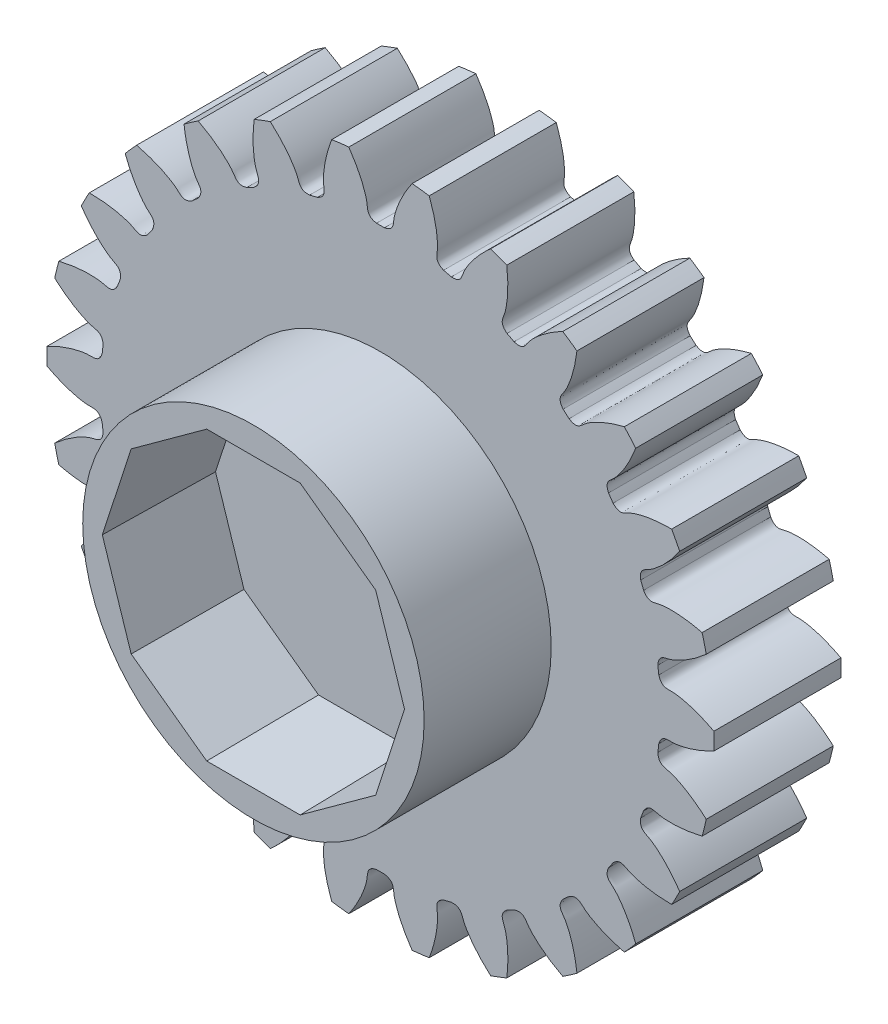
SolidWorks part; units mm, degrees
ref_plane "前视基准面" through (0, 0, 0) normal (0, 0, 1) x (1, 0, 0)
ref_plane "上视基准面" through (0, 0, 0) normal (0, 1, 0) x (1, 0, 0)
ref_plane "右视基准面" through (0, 0, 0) normal (1, 0, 0) x (0, 0, -1)
sketch "草图1" plane through (0, 0, 0) normal (0, 0, 1) x (1, 0, 0)
  circle A0 centre (0, 0) radius 21
extrude "凸台-拉伸1" add sketch "草图1" along normal blind 10
ref_axis "基准轴1" through (0, 0, -0.5) along (0, 0, 1)
sketch "草图2" plane through (0, 0, 0) normal (0, 0, 1) x (1, 0, 0)
  line L0 (0, 0) -> (0, 21) construction
  circle A0 centre (0, 0) radius 21 construction
  arc A1 (0.2506, 17.6232) -> (-0.2506, 17.6232) centre (0, 0) ccw
  arc A2 (4.9424, 23.9032) -> (-4.9424, 23.9032) centre (0, 0) ccw
  spline S0 degree 3 poles (0.2506, 17.6232) (0.8447, 17.7357) (0.7955, 18.0869) (0.8511, 18.4383) (0.8595, 18.4852) (0.8702, 18.5391) (0.8835, 18.6) (0.8998, 18.6677) (0.9193, 18.7421) (0.9423, 18.8232) (0.969, 18.9109) (0.9997, 19.0049) (1.0348, 19.1053) (1.0744, 19.2118) (1.1188, 19.3243) (1.1682, 19.4426) (1.223, 19.5667) (1.2833, 19.6962) (1.3495, 19.8312) (1.4217, 19.9713) (1.5001, 20.1163) (1.5851, 20.2662) (1.6767, 20.4206) (1.7754, 20.5794) (1.8811, 20.7423) (1.9942, 20.9092) (2.1149, 21.0797) (2.2433, 21.2537) (2.3796, 21.4309) (2.524, 21.6111) (2.6767, 21.7939) (2.8378, 21.9792) (3.0075, 22.1667) (3.186, 22.3561) (3.3733, 22.5471) (3.5696, 22.7394) (3.7751, 22.9329) (3.9899, 23.127) (4.214, 23.3217) (4.5293, 23.5846) (4.7745, 23.7768) (4.9424, 23.9032) knots 0 0 0 0 0.122665 0.127715 0.133684 0.14057 0.148375 0.157098 0.166739 0.177298 0.188775 0.201171 0.214485 0.228717 0.243867 0.259935 0.276922 0.294827 0.31365 0.333391 0.35405 0.375628 0.398124 0.421538 0.44587 0.47112 0.497289 0.524375 0.55238 0.581303 0.611145 0.641904 0.673582 0.706178 0.739692 0.774124 0.809475 0.845743 0.88293 0.921035 1 1 1 1
  spline S1 degree 3 poles (-0.2506, 17.6232) (-0.8447, 17.7357) (-0.7955, 18.0869) (-0.8511, 18.4383) (-0.8595, 18.4852) (-0.8702, 18.5391) (-0.8835, 18.6) (-0.8998, 18.6677) (-0.9193, 18.7421) (-0.9423, 18.8232) (-0.969, 18.9109) (-0.9997, 19.0049) (-1.0348, 19.1053) (-1.0744, 19.2118) (-1.1188, 19.3243) (-1.1682, 19.4426) (-1.223, 19.5667) (-1.2833, 19.6962) (-1.3495, 19.8312) (-1.4217, 19.9713) (-1.5001, 20.1163) (-1.5851, 20.2662) (-1.6767, 20.4206) (-1.7754, 20.5794) (-1.8811, 20.7423) (-1.9942, 20.9092) (-2.1149, 21.0797) (-2.2433, 21.2537) (-2.3796, 21.4309) (-2.524, 21.6111) (-2.6767, 21.7939) (-2.8378, 21.9792) (-3.0075, 22.1667) (-3.186, 22.3561) (-3.3733, 22.5471) (-3.5696, 22.7394) (-3.7751, 22.9329) (-3.9899, 23.127) (-4.214, 23.3217) (-4.5293, 23.5846) (-4.7745, 23.7768) (-4.9424, 23.9032) knots 0 0 0 0 0.122665 0.127715 0.133684 0.14057 0.148375 0.157098 0.166739 0.177298 0.188775 0.201171 0.214485 0.228717 0.243867 0.259935 0.276922 0.294827 0.31365 0.333391 0.35405 0.375628 0.398124 0.421538 0.44587 0.47112 0.497289 0.524375 0.55238 0.581303 0.611145 0.641904 0.673582 0.706178 0.739692 0.774124 0.809475 0.845743 0.88293 0.921035 1 1 1 1
extrude "切除-拉伸1" cut sketch "草图2" along normal through all
pattern_circular "阵列(圆周)1" count 26 every 13.846 about axis through (0, 0, -0.5) along (0, 0, 1) of "切除-拉伸1"
sketch "草图3" plane through (0, 0, 0) normal (0, 0, 1) x (1, 0, 0)
  circle A0 centre (0, 0) radius 19.5 construction
  dimension "Dn" = 39
sketch "草图4" plane through (0, 0, 10) normal (0, 0, 1) x (1, 0, 0)
  line L1 (9.5157, 0) -> (7.6984, 5.5932)
  line L2 (7.6984, 5.5932) -> (2.9405, 9.05)
  line L3 (2.9405, 9.05) -> (-2.9405, 9.05)
  line L4 (-2.9405, 9.05) -> (-7.6984, 5.5932)
  line L5 (-7.6984, 5.5932) -> (-9.5157, 0)
  line L6 (-9.5157, 0) -> (-7.6984, -5.5932)
  line L7 (-7.6984, -5.5932) -> (-2.9405, -9.05)
  line L8 (-2.9405, -9.05) -> (2.9405, -9.05)
  line L9 (2.9405, -9.05) -> (7.6984, -5.5932)
  line L10 (7.6984, -5.5932) -> (9.5157, 0)
  circle A0 centre (0, 0) radius 9.05 construction
  dimension "D1" = 18.1
extrude "切除-拉伸2" cut sketch "草图4" against normal blind 8 draft 1
sketch "草图5" plane through (0, 0, 0) normal (0, 0, -1) x (-1, 0, 0)
  arc A52 (4.4609, 17.0511) -> (3.9742, 17.1711) centre (0, 0) ccw
  arc A53 (3.0685, 20.7746) -> (1.9924, 20.9053) centre (0, 0) ccw
  arc A54 (0.2506, 17.6232) -> (-0.2506, 17.6232) centre (0, 0) ccw
  arc A55 (-1.9924, 20.9053) -> (-3.0685, 20.7746) centre (0, 0) ccw
  arc A56 (-3.9742, 17.1711) -> (-4.4609, 17.0511) centre (0, 0) ccw
  arc A57 (-6.9374, 19.821) -> (-7.951, 19.4366) centre (0, 0) ccw
  arc A58 (-7.968, 15.7211) -> (-8.4118, 15.4881) centre (0, 0) ccw
  arc A59 (-11.4793, 17.5848) -> (-12.3715, 16.969) centre (0, 0) ccw
  arc A60 (-11.4988, 13.3574) -> (-11.874, 13.025) centre (0, 0) ccw
  arc A61 (-15.3541, 14.3266) -> (-16.0729, 13.5152) centre (0, 0) ccw
  arc A62 (-14.3613, 10.2174) -> (-14.646, 9.8049) centre (0, 0) ccw
  arc A63 (-18.3365, 10.2359) -> (-18.8403, 9.276) centre (0, 0) ccw
  arc A64 (-16.3891, 6.4836) -> (-16.5669, 6.0149) centre (0, 0) ccw
  arc A65 (-20.2533, 5.5502) -> (-20.5127, 4.4977) centre (0, 0) ccw
  arc A66 (-17.4645, 2.373) -> (-17.5249, 1.8754) centre (0, 0) ccw
  arc A67 (-20.993, 0.542) -> (-20.993, -0.542) centre (0, 0) ccw
  arc A68 (-17.5249, -1.8754) -> (-17.4645, -2.373) centre (0, 0) ccw
  arc A69 (-20.5127, -4.4977) -> (-20.2533, -5.5502) centre (0, 0) ccw
  arc A70 (-16.5669, -6.0149) -> (-16.3891, -6.4836) centre (0, 0) ccw
  arc A71 (-18.8403, -9.276) -> (-18.3365, -10.2359) centre (0, 0) ccw
  arc A72 (-14.646, -9.8049) -> (-14.3613, -10.2174) centre (0, 0) ccw
  arc A73 (-16.0729, -13.5152) -> (-15.3541, -14.3266) centre (0, 0) ccw
  arc A74 (-11.874, -13.025) -> (-11.4988, -13.3574) centre (0, 0) ccw
  arc A75 (-12.3715, -16.969) -> (-11.4793, -17.5848) centre (0, 0) ccw
  arc A76 (-8.4118, -15.4881) -> (-7.968, -15.7211) centre (0, 0) ccw
  arc A77 (-7.951, -19.4366) -> (-6.9374, -19.821) centre (0, 0) ccw
  arc A78 (-4.4609, -17.0511) -> (-3.9742, -17.1711) centre (0, 0) ccw
  arc A79 (-3.0685, -20.7746) -> (-1.9924, -20.9053) centre (0, 0) ccw
  arc A80 (-0.2506, -17.6232) -> (0.2506, -17.6232) centre (0, 0) ccw
  arc A81 (1.9924, -20.9053) -> (3.0685, -20.7746) centre (0, 0) ccw
  arc A82 (3.9742, -17.1711) -> (4.4609, -17.0511) centre (0, 0) ccw
  arc A83 (6.9374, -19.821) -> (7.951, -19.4366) centre (0, 0) ccw
  arc A84 (7.968, -15.7211) -> (8.4118, -15.4881) centre (0, 0) ccw
  arc A85 (11.4793, -17.5848) -> (12.3715, -16.969) centre (0, 0) ccw
  arc A86 (11.4988, -13.3574) -> (11.874, -13.025) centre (0, 0) ccw
  arc A87 (15.3541, -14.3266) -> (16.0729, -13.5152) centre (0, 0) ccw
  arc A88 (14.3613, -10.2174) -> (14.646, -9.8049) centre (0, 0) ccw
  arc A89 (18.3365, -10.2359) -> (18.8403, -9.276) centre (0, 0) ccw
  arc A90 (16.3891, -6.4836) -> (16.5669, -6.0149) centre (0, 0) ccw
  arc A91 (20.2533, -5.5502) -> (20.5127, -4.4977) centre (0, 0) ccw
  arc A92 (17.4645, -2.373) -> (17.5249, -1.8754) centre (0, 0) ccw
  arc A93 (20.993, -0.542) -> (20.993, 0.542) centre (0, 0) ccw
  arc A94 (17.5249, 1.8754) -> (17.4645, 2.373) centre (0, 0) ccw
  arc A95 (20.5127, 4.4977) -> (20.2533, 5.5502) centre (0, 0) ccw
  arc A96 (16.5669, 6.0149) -> (16.3891, 6.4836) centre (0, 0) ccw
  arc A97 (18.8403, 9.276) -> (18.3365, 10.2359) centre (0, 0) ccw
  arc A98 (14.646, 9.8049) -> (14.3613, 10.2174) centre (0, 0) ccw
  arc A99 (16.0729, 13.5152) -> (15.3541, 14.3266) centre (0, 0) ccw
  arc A100 (11.874, 13.025) -> (11.4988, 13.3574) centre (0, 0) ccw
  arc A101 (12.3715, 16.969) -> (11.4793, 17.5848) centre (0, 0) ccw
  arc A102 (8.4118, 15.4881) -> (7.968, 15.7211) centre (0, 0) ccw
  arc A103 (7.951, 19.4366) -> (6.9374, 19.821) centre (0, 0) ccw
  arc A104 (4.4609, 17.0511) -> (3.9742, 17.1711) centre (0, 0) ccw
  arc A105 (3.0685, 20.7746) -> (1.9924, 20.9053) centre (0, 0) ccw
  arc A106 (0.2506, 17.6232) -> (-0.2506, 17.6232) centre (0, 0) ccw
  arc A107 (-1.9924, 20.9053) -> (-3.0685, 20.7746) centre (0, 0) ccw
  arc A108 (-3.9742, 17.1711) -> (-4.4609, 17.0511) centre (0, 0) ccw
  arc A109 (-6.9374, 19.821) -> (-7.951, 19.4366) centre (0, 0) ccw
  arc A110 (-7.968, 15.7211) -> (-8.4118, 15.4881) centre (0, 0) ccw
  arc A111 (-11.4793, 17.5848) -> (-12.3715, 16.969) centre (0, 0) ccw
  arc A112 (-11.4988, 13.3574) -> (-11.874, 13.025) centre (0, 0) ccw
  arc A113 (-15.3541, 14.3266) -> (-16.0729, 13.5152) centre (0, 0) ccw
  arc A114 (-14.3613, 10.2174) -> (-14.646, 9.8049) centre (0, 0) ccw
  arc A115 (-18.3365, 10.2359) -> (-18.8403, 9.276) centre (0, 0) ccw
  arc A116 (-16.3891, 6.4836) -> (-16.5669, 6.0149) centre (0, 0) ccw
  arc A117 (-20.2533, 5.5502) -> (-20.5127, 4.4977) centre (0, 0) ccw
  arc A118 (-17.4645, 2.373) -> (-17.5249, 1.8754) centre (0, 0) ccw
  arc A119 (-20.993, 0.542) -> (-20.993, -0.542) centre (0, 0) ccw
  arc A120 (-17.5249, -1.8754) -> (-17.4645, -2.373) centre (0, 0) ccw
  arc A121 (-20.5127, -4.4977) -> (-20.2533, -5.5502) centre (0, 0) ccw
  arc A122 (-16.5669, -6.0149) -> (-16.3891, -6.4836) centre (0, 0) ccw
  arc A123 (-18.8403, -9.276) -> (-18.3365, -10.2359) centre (0, 0) ccw
  arc A124 (-14.646, -9.8049) -> (-14.3613, -10.2174) centre (0, 0) ccw
  arc A125 (-16.0729, -13.5152) -> (-15.3541, -14.3266) centre (0, 0) ccw
  arc A126 (-11.874, -13.025) -> (-11.4988, -13.3574) centre (0, 0) ccw
  arc A127 (-12.3715, -16.969) -> (-11.4793, -17.5848) centre (0, 0) ccw
  arc A128 (-8.4118, -15.4881) -> (-7.968, -15.7211) centre (0, 0) ccw
  arc A129 (-7.951, -19.4366) -> (-6.9374, -19.821) centre (0, 0) ccw
  arc A130 (-4.4609, -17.0511) -> (-3.9742, -17.1711) centre (0, 0) ccw
  arc A131 (-3.0685, -20.7746) -> (-1.9924, -20.9053) centre (0, 0) ccw
  arc A132 (-0.2506, -17.6232) -> (0.2506, -17.6232) centre (0, 0) ccw
  arc A133 (1.9924, -20.9053) -> (3.0685, -20.7746) centre (0, 0) ccw
  arc A134 (3.9742, -17.1711) -> (4.4609, -17.0511) centre (0, 0) ccw
  arc A135 (6.9374, -19.821) -> (7.951, -19.4366) centre (0, 0) ccw
  arc A136 (7.968, -15.7211) -> (8.4118, -15.4881) centre (0, 0) ccw
  arc A137 (11.4793, -17.5848) -> (12.3715, -16.969) centre (0, 0) ccw
  arc A138 (11.4988, -13.3574) -> (11.874, -13.025) centre (0, 0) ccw
  arc A139 (15.3541, -14.3266) -> (16.0729, -13.5152) centre (0, 0) ccw
  arc A140 (14.3613, -10.2174) -> (14.646, -9.8049) centre (0, 0) ccw
  arc A141 (18.3365, -10.2359) -> (18.8403, -9.276) centre (0, 0) ccw
  arc A142 (16.3891, -6.4836) -> (16.5669, -6.0149) centre (0, 0) ccw
  arc A143 (20.2533, -5.5502) -> (20.5127, -4.4977) centre (0, 0) ccw
  arc A144 (17.4645, -2.373) -> (17.5249, -1.8754) centre (0, 0) ccw
  arc A145 (20.993, -0.542) -> (20.993, 0.542) centre (0, 0) ccw
  arc A146 (17.5249, 1.8754) -> (17.4645, 2.373) centre (0, 0) ccw
  arc A147 (20.5127, 4.4977) -> (20.2533, 5.5502) centre (0, 0) ccw
  arc A148 (16.5669, 6.0149) -> (16.3891, 6.4836) centre (0, 0) ccw
  arc A149 (18.8403, 9.276) -> (18.3365, 10.2359) centre (0, 0) ccw
  arc A150 (14.646, 9.8049) -> (14.3613, 10.2174) centre (0, 0) ccw
  arc A151 (16.0729, 13.5152) -> (15.3541, 14.3266) centre (0, 0) ccw
  arc A152 (11.874, 13.025) -> (11.4988, 13.3574) centre (0, 0) ccw
  arc A153 (12.3715, 16.969) -> (11.4793, 17.5848) centre (0, 0) ccw
  arc A154 (8.4118, 15.4881) -> (7.968, 15.7211) centre (0, 0) ccw
  arc A155 (7.951, 19.4366) -> (6.9374, 19.821) centre (0, 0) ccw
  spline S52 degree 3 poles (-3831.2582, 1145.2571) (200.7619, -78.8933) (32.1838, 44.9612) (6.3928, 19.3044) (6.1635, 19.0573) (5.9926, 18.8577) (5.8433, 18.6721) (5.737, 18.5319) (5.6408, 18.3964) (5.5769, 18.3025) (5.5189, 18.2134) (5.4665, 18.1295) (5.4196, 18.0508) (5.3779, 17.9775) (5.3411, 17.9099) (5.3091, 17.848) (5.2746, 17.7779) (5.2461, 17.7157) (3.021, 12.4321) (27.6877, -3.9546) (-3392.9144, 2126.5464) knots -13.002555 -13.002555 -13.002555 -13.002555 0.578462 0.624372 0.666609 0.705173 0.723078 0.756133 0.771283 0.785515 0.798829 0.811225 0.822702 0.833261 0.842902 0.851625 0.85943 0.872285 0.877335 3.013928 3.013928 3.013928 3.013928 only from (6.9374, 19.821) to (4.4609, 17.0511)
  spline S53 degree 3 poles (3992.7038, 306.2101) (-26.3549, 9.3654) (3.1025, 12.4119) (3.5877, 18.1244) (3.5914, 18.1928) (3.5934, 18.2709) (3.5938, 18.3406) (3.5927, 18.4175) (3.5898, 18.5018) (3.5848, 18.5932) (3.5775, 18.6919) (3.5637, 18.8379) (3.5385, 19.0379) (3.4952, 19.2982) (3.4355, 19.5853) (3.3573, 19.8983) (3.2585, 20.236) (-8.6488, 55.615) (-217.8358, 20.0949) (3925.0939, -763.8862) knots -2.013959 -2.013959 -2.013959 -2.013959 0.122665 0.127715 0.14057 0.148375 0.157098 0.166739 0.177298 0.188775 0.201171 0.214485 0.243867 0.276922 0.31365 0.35405 0.398124 0.44587 14.380112 14.380112 14.380112 14.380112 only from (3.9742, 17.1711) to (3.0685, 20.7746)
  spline S54 degree 3 poles (-3994.0067, 195.0979) (213.8085, -28.5553) (20.4887, 51.3568) (1.5872, 20.2734) (1.4237, 19.9785) (1.3055, 19.7439) (1.2049, 19.5279) (1.1354, 19.3663) (1.0744, 19.2118) (1.0348, 19.1053) (0.9997, 19.0049) (0.969, 18.9109) (0.9423, 18.8232) (0.9193, 18.7421) (0.8998, 18.6677) (0.8835, 18.6) (0.8668, 18.5236) (0.854, 18.4564) (-0.042, 12.7938) (27.8296, 2.7864) (-3803.2384, 1252.7753) knots -13.002555 -13.002555 -13.002555 -13.002555 0.578462 0.624372 0.666609 0.705173 0.723078 0.756133 0.771283 0.785515 0.798829 0.811225 0.822702 0.833261 0.842902 0.851625 0.85943 0.872285 0.877335 3.013928 3.013928 3.013928 3.013928 only from (1.9924, 20.9053) to (0.2506, 17.6232)
  spline S55 degree 3 poles (3803.4022, 1252.8287) (-27.8304, 2.7861) (0.042, 12.7937) (-0.854, 18.4564) (-0.8668, 18.5236) (-0.8835, 18.6) (-0.8998, 18.6677) (-0.9193, 18.7421) (-0.9423, 18.8232) (-0.969, 18.9109) (-0.9997, 19.0049) (-1.0481, 19.1433) (-1.1204, 19.3315) (-1.2248, 19.5739) (-1.3514, 19.8384) (-1.5022, 20.1236) (-1.679, 20.4278) (-21.707, 51.9292) (-216.315, -32.6206) (3993.8477, 197.6474) knots -2.013959 -2.013959 -2.013959 -2.013959 0.122665 0.127715 0.14057 0.148375 0.157098 0.166739 0.177298 0.188775 0.201171 0.214485 0.243867 0.276922 0.31365 0.35405 0.398124 0.44587 14.380112 14.380112 14.380112 14.380112 only from (-0.2506, 17.6232) to (-1.9924, 20.9053)
  spline S56 degree 3 poles (-3924.6381, -766.3996) (214.4293, 23.4422) (7.6028, 54.7678) (-3.3106, 20.0641) (-3.3989, 19.7387) (-3.4574, 19.4826) (-3.5034, 19.2488) (-3.5323, 19.0753) (-3.5545, 18.9106) (-3.5675, 18.7977) (-3.5775, 18.6919) (-3.5848, 18.5932) (-3.5898, 18.5018) (-3.5927, 18.4175) (-3.5938, 18.3406) (-3.5934, 18.2709) (-3.5914, 18.1928) (-3.5877, 18.1244) (-3.1025, 12.412) (26.3541, 9.3655) (-3992.5319, 306.1974) knots -13.002555 -13.002555 -13.002555 -13.002555 0.578462 0.624372 0.666609 0.705173 0.723078 0.756133 0.771283 0.785515 0.798829 0.811225 0.822702 0.833261 0.842902 0.851625 0.85943 0.872285 0.877335 3.013928 3.013928 3.013928 3.013928 only from (-3.0685, 20.7746) to (-3.9742, 17.1711)
  spline S57 degree 3 poles (3393.0607, 2126.6375) (-27.6884, -3.9551) (-3.021, 12.432) (-5.2461, 17.7157) (-5.2746, 17.7779) (-5.3091, 17.848) (-5.3411, 17.9099) (-5.3779, 17.9775) (-5.4196, 18.0508) (-5.4665, 18.1295) (-5.5189, 18.2134) (-5.5989, 18.3362) (-5.7141, 18.5017) (-5.8735, 18.712) (-6.0598, 18.9385) (-6.2744, 19.1793) (-6.5189, 19.4324) (-33.5037, 45.2254) (-202.2226, -83.4402) (3830.4936, 1147.6944) knots -2.013959 -2.013959 -2.013959 -2.013959 0.122665 0.127715 0.14057 0.148375 0.157098 0.166739 0.177298 0.188775 0.201171 0.214485 0.243867 0.276922 0.31365 0.35405 0.398124 0.44587 14.380112 14.380112 14.380112 14.380112 only from (-4.4609, 17.0511) to (-6.9374, 19.821)
  spline S58 degree 3 poles (-3627.1839, -1683.3568) (202.5883, 74.0773) (-5.7249, 54.9958) (-8.0161, 18.6888) (-8.0239, 18.3517) (-8.0195, 18.089) (-8.0081, 17.8511) (-7.9947, 17.6756) (-7.9768, 17.5105) (-7.9624, 17.3978) (-7.9468, 17.2926) (-7.9303, 17.1951) (-7.9132, 17.105) (-7.8959, 17.0225) (-7.8785, 16.9476) (-7.8615, 16.88) (-7.8409, 16.8046) (-7.821, 16.7392) (-5.9827, 11.3088) (23.3469, 15.4003) (-3949.794, -658.1756) knots -13.002555 -13.002555 -13.002555 -13.002555 0.578462 0.624372 0.666609 0.705173 0.723078 0.756133 0.771283 0.785515 0.798829 0.811225 0.822702 0.833261 0.842902 0.851625 0.85943 0.872285 0.877335 3.013928 3.013928 3.013928 3.013928 only from (-7.951, 19.4366) to (-7.968, 15.7211)
  spline S59 degree 3 poles (2785.5269, 2876.8539) (-25.9373, -10.4664) (-5.9083, 11.3478) (-9.3333, 15.9455) (-9.3758, 15.999) (-9.4262, 16.0588) (-9.472, 16.1112) (-9.5239, 16.1681) (-9.5819, 16.2292) (-9.6463, 16.2944) (-9.7173, 16.3634) (-9.8244, 16.4635) (-9.9758, 16.5966) (-10.1809, 16.7627) (-10.416, 16.938) (-10.682, 17.1204) (-10.9799, 17.3077) (-43.3533, 35.8933) (-176.3778, -129.4107) (3444.5252, 2031.0416) knots -2.013959 -2.013959 -2.013959 -2.013959 0.122665 0.127715 0.14057 0.148375 0.157098 0.166739 0.177298 0.188775 0.201171 0.214485 0.243867 0.276922 0.31365 0.35405 0.398124 0.44587 14.380112 14.380112 14.380112 14.380112 only from (-8.4118, 15.4881) to (-11.4793, 17.5848)
  spline S60 degree 3 poles (-3118.9308, -2502.4835) (178.9736, 120.4073) (-18.7199, 52.0276) (-12.2557, 16.2274) (-12.1826, 15.8982) (-12.1154, 15.6442) (-12.0475, 15.4159) (-11.9924, 15.2488) (-11.9356, 15.0926) (-11.8946, 14.9867) (-11.8543, 14.8883) (-11.8149, 14.7976) (-11.7768, 14.7142) (-11.7402, 14.6383) (-11.7054, 14.5696) (-11.6727, 14.5082) (-11.6346, 14.4399) (-11.5996, 14.3811) (-8.5153, 9.5484) (18.983, 20.5401) (-3677.5085, -1584.2978) knots -13.002555 -13.002555 -13.002555 -13.002555 0.578462 0.624372 0.666609 0.705173 0.723078 0.756133 0.771283 0.785515 0.798829 0.811225 0.822702 0.833261 0.842902 0.851625 0.85943 0.872285 0.877335 3.013928 3.013928 3.013928 3.013928 only from (-12.3715, 16.969) to (-11.4988, 13.3574)
  spline S61 degree 3 poles (2016.1083, 3459.878) (-22.6789, -16.3695) (-8.4524, 9.6041) (-12.878, 13.2485) (-12.9322, 13.2903) (-12.9954, 13.3364) (-13.0525, 13.3763) (-13.1164, 13.4191) (-13.1874, 13.4645) (-13.2655, 13.5124) (-13.3509, 13.5624) (-13.4789, 13.634) (-13.6578, 13.7269) (-13.8967, 13.8391) (-14.1668, 13.9531) (-14.4688, 14.0666) (-14.8029, 14.1771) (-50.6834, 24.4751) (-140.2826, -167.8602) (2858.3735, 2796.3521) knots -2.013959 -2.013959 -2.013959 -2.013959 0.122665 0.127715 0.14057 0.148375 0.157098 0.166739 0.177298 0.188775 0.201171 0.214485 0.243867 0.276922 0.31365 0.35405 0.398124 0.44587 14.380112 14.380112 14.380112 14.380112 only from (-11.874, 13.025) to (-15.3541, 14.3266)
  spline S62 degree 3 poles (-2429.4169, -3176.1748) (144.9576, 159.7397) (-30.627, 46.0359) (-15.783, 12.8229) (-15.6332, 12.5207) (-15.5073, 12.2902) (-15.3867, 12.0848) (-15.2932, 11.9357) (-15.2007, 11.7977) (-15.1355, 11.7046) (-15.0728, 11.6188) (-15.0129, 11.5401) (-14.9559, 11.4683) (-14.9022, 11.4033) (-14.852, 11.345) (-14.8056, 11.2931) (-14.7522, 11.2359) (-14.7042, 11.1872) (-10.5529, 7.2331) (13.5158, 24.4862) (-3191.4995, -2418.3464) knots -13.002555 -13.002555 -13.002555 -13.002555 0.578462 0.624372 0.666609 0.705173 0.723078 0.756133 0.771283 0.785515 0.798829 0.811225 0.822702 0.833261 0.842902 0.851625 0.85943 0.872285 0.877335 3.013928 3.013928 3.013928 3.013928 only from (-16.0729, 13.5152) to (-14.3613, 10.2174)
  spline S63 degree 3 poles (1129.5209, 3841.8265) (-18.1024, -21.3212) (-10.5052, 7.3022) (-15.6744, 9.7816) (-15.737, 9.8093) (-15.8094, 9.8388) (-15.8743, 9.8639) (-15.9467, 9.8902) (-16.0265, 9.9173) (-16.1138, 9.9451) (-16.2087, 9.9732) (-16.35, 10.0121) (-16.546, 10.0595) (-16.8048, 10.1113) (-17.0944, 10.1573) (-17.4147, 10.1952) (-17.7655, 10.2225) (-55.0679, 11.6346) (-96.0347, -196.5543) (2106.1035, 3399.1487) knots -2.013959 -2.013959 -2.013959 -2.013959 0.122665 0.127715 0.14057 0.148375 0.157098 0.166739 0.177298 0.188775 0.201171 0.214485 0.243867 0.276922 0.31365 0.35405 0.398124 0.44587 14.380112 14.380112 14.380112 14.380112 only from (-14.646, 9.8049) to (-18.3365, 10.2359)
  spline S64 degree 3 poles (-1598.714, -3665.2785) (102.5172, 189.7886) (-40.7541, 37.3686) (-18.3931, 8.6731) (-18.1754, 8.4156) (-17.9979, 8.2219) (-17.8316, 8.0513) (-17.7052, 7.929) (-17.5823, 7.8171) (-17.4968, 7.7424) (-17.4154, 7.674) (-17.3384, 7.6119) (-17.2659, 7.5559) (-17.1982, 7.5056) (-17.1355, 7.461) (-17.078, 7.4218) (-17.0125, 7.379) (-16.9542, 7.3432) (-11.9773, 4.4975) (7.2631, 27.0092) (-2520.0121, -3111.8494) knots -13.002555 -13.002555 -13.002555 -13.002555 0.578462 0.624372 0.666609 0.705173 0.723078 0.756133 0.771283 0.785515 0.798829 0.811225 0.822702 0.833261 0.842902 0.851625 0.85943 0.872285 0.877335 3.013928 3.013928 3.013928 3.013928 only from (-18.8403, 9.276) to (-16.3891, 6.4836)
  spline S65 degree 3 poles (177.2898, 4000.502) (-12.4739, -25.0339) (-11.9474, 4.576) (-17.5598, 5.7462) (-17.6272, 5.7581) (-17.7046, 5.7695) (-17.7736, 5.7783) (-17.8502, 5.7865) (-17.9342, 5.7938) (-18.0256, 5.7999) (-18.1244, 5.8045) (-18.271, 5.8084) (-18.4726, 5.8075) (-18.7362, 5.7958) (-19.0284, 5.7712) (-19.3485, 5.7313) (-19.6957, 5.6739) (-56.252, -1.8821) (-46.2056, -213.8254) (1231.4344, 3804.3992) knots -2.013959 -2.013959 -2.013959 -2.013959 0.122665 0.127715 0.14057 0.148375 0.157098 0.166739 0.177298 0.188775 0.201171 0.214485 0.243867 0.276922 0.31365 0.35405 0.398124 0.44587 14.380112 14.380112 14.380112 14.380112 only from (-16.5669, 6.0149) to (-20.2533, 5.5502)
  spline S66 degree 3 poles (-675.0998, -3941.3695) (54.1189, 208.8076) (-48.5127, 26.5297) (-19.9343, 4.0193) (-19.6612, 3.8214) (-19.4425, 3.6758) (-19.2403, 3.55) (-19.0883, 3.4614) (-18.9422, 3.3823) (-18.8412, 3.3301) (-18.7458, 3.2832) (-18.6562, 3.2414) (-18.5724, 3.2043) (-18.4947, 3.1717) (-18.4231, 3.1434) (-18.3578, 3.1191) (-18.2841, 3.0932) (-18.2189, 3.0724) (-12.7056, 1.5004) (0.5884, 27.9625) (-1702.0708, -3624.5031) knots -13.002555 -13.002555 -13.002555 -13.002555 0.578462 0.624372 0.666609 0.705173 0.723078 0.756133 0.771283 0.785515 0.798829 0.811225 0.822702 0.833261 0.842902 0.851625 0.85943 0.872285 0.877335 3.013928 3.013928 3.013928 3.013928 only from (-20.5127, 4.4977) to (-17.4645, 2.373)
  spline S67 degree 3 poles (-785.2447, 3926.683) (-6.1204, -27.2916) (-12.6954, 1.5838) (-18.4247, 1.3769) (-18.493, 1.3723) (-18.5708, 1.3649) (-18.64, 1.3569) (-18.7163, 1.3465) (-18.7996, 1.3335) (-18.8898, 1.3175) (-18.9869, 1.2983) (-19.1301, 1.267) (-19.3256, 1.218) (-19.5788, 1.1435) (-19.8567, 1.0497) (-20.1579, 0.9344) (-20.4812, 0.7956) (-54.1671, -15.2894) (6.3089, -218.6697) (285.1988, 3988.5518) knots -2.013959 -2.013959 -2.013959 -2.013959 0.122665 0.127715 0.14057 0.148375 0.157098 0.166739 0.177298 0.188775 0.201171 0.214485 0.243867 0.276922 0.31365 0.35405 0.398124 0.44587 14.380112 14.380112 14.380112 14.380112 only from (-17.5249, 1.8754) to (-20.993, 0.542)
  spline S68 degree 3 poles (287.7489, -3988.4024) (2.5753, 215.6915) (-53.452, 14.1489) (-20.3169, -0.868) (-20.0044, -0.9949) (-19.7573, -1.0839) (-19.5308, -1.1577) (-19.362, -1.2073) (-19.2012, -1.2492) (-19.0907, -1.2756) (-18.9869, -1.2983) (-18.8898, -1.3175) (-18.7996, -1.3335) (-18.7163, -1.3465) (-18.64, -1.3569) (-18.5708, -1.3649) (-18.493, -1.3723) (-18.4247, -1.3769) (-12.6954, -1.5838) (-6.1206, 27.2908) (-785.2114, -3926.5138) knots -13.002555 -13.002555 -13.002555 -13.002555 0.578462 0.624372 0.666609 0.705173 0.723078 0.756133 0.771283 0.785515 0.798829 0.811225 0.822702 0.833261 0.842902 0.851625 0.85943 0.872285 0.877335 3.013928 3.013928 3.013928 3.013928 only from (-20.993, -0.542) to (-17.5249, -1.8754)
  spline S69 degree 3 poles (-1702.1437, 3624.6593) (0.5887, -27.9633) (-12.7055, -1.5004) (-18.2189, -3.0724) (-18.2841, -3.0932) (-18.3578, -3.1191) (-18.4231, -3.1434) (-18.4947, -3.1717) (-18.5724, -3.2043) (-18.6562, -3.2414) (-18.7458, -3.2832) (-18.8774, -3.3479) (-19.0555, -3.4424) (-19.2836, -3.5752) (-19.5309, -3.7328) (-19.7958, -3.9169) (-20.0765, -4.129) (-48.9341, -27.8081) (58.4566, -210.8058) (-677.6115, 3940.9043) knots -2.013959 -2.013959 -2.013959 -2.013959 0.122665 0.127715 0.14057 0.148375 0.157098 0.166739 0.177298 0.188775 0.201171 0.214485 0.243867 0.276922 0.31365 0.35405 0.398124 0.44587 14.380112 14.380112 14.380112 14.380112 only from (-17.4645, -2.373) to (-20.5127, -4.4977)
  spline S70 degree 3 poles (1233.8746, -3803.6439) (-49.1179, 210.0403) (-55.2849, 0.9459) (-19.5188, -5.705) (-19.1851, -5.7533) (-18.9238, -5.7806) (-18.6862, -5.798) (-18.5104, -5.8058) (-18.3443, -5.808) (-18.2307, -5.8073) (-18.1244, -5.8045) (-18.0256, -5.7999) (-17.9342, -5.7938) (-17.8502, -5.7865) (-17.7736, -5.7783) (-17.7046, -5.7695) (-17.6272, -5.7581) (-17.5598, -5.7462) (-11.9475, -4.576) (-12.4739, 25.033) (177.2817, -4000.3299) knots -13.002555 -13.002555 -13.002555 -13.002555 0.578462 0.624372 0.666609 0.705173 0.723078 0.756133 0.771283 0.785515 0.798829 0.811225 0.822702 0.833261 0.842902 0.851625 0.85943 0.872285 0.877335 3.013928 3.013928 3.013928 3.013928 only from (-20.2533, -5.5502) to (-16.5669, -6.0149)
  spline S71 degree 3 poles (-2520.1202, 3111.9837) (7.2637, -27.0098) (-11.9772, -4.4974) (-16.9542, -7.3432) (-17.0125, -7.379) (-17.078, -7.4218) (-17.1355, -7.461) (-17.1982, -7.5056) (-17.2659, -7.5559) (-17.3384, -7.6119) (-17.4154, -7.674) (-17.5277, -7.7683) (-17.678, -7.9026) (-17.8676, -8.0862) (-18.07, -8.2984) (-18.2832, -8.5405) (-18.505, -8.8137) (-40.8572, -38.7108) (107.2071, -190.6906) (-1601.0414, 3664.2258) knots -2.013959 -2.013959 -2.013959 -2.013959 0.122665 0.127715 0.14057 0.148375 0.157098 0.166739 0.177298 0.188775 0.201171 0.214485 0.243867 0.276922 0.31365 0.35405 0.398124 0.44587 14.380112 14.380112 14.380112 14.380112 only from (-16.3891, -6.4836) to (-18.8403, -9.276)
  spline S72 degree 3 poles (2108.292, -3397.8314) (-97.9565, 192.1822) (-53.9047, -12.3122) (-17.5863, -10.2103) (-17.2507, -10.1774) (-16.9905, -10.1414) (-16.7556, -10.1015) (-16.5831, -10.0669) (-16.4213, -10.0293) (-16.3111, -10.0014) (-16.2087, -9.9732) (-16.1138, -9.9451) (-16.0265, -9.9173) (-15.9467, -9.8902) (-15.8743, -9.8639) (-15.8094, -9.8388) (-15.737, -9.8093) (-15.6744, -9.7816) (-10.5052, -7.3023) (-18.1022, 21.3204) (1129.4718, -3841.6613) knots -13.002555 -13.002555 -13.002555 -13.002555 0.578462 0.624372 0.666609 0.705173 0.723078 0.756133 0.771283 0.785515 0.798829 0.811225 0.822702 0.833261 0.842902 0.851625 0.85943 0.872285 0.877335 3.013928 3.013928 3.013928 3.013928 only from (-18.3365, -10.2359) to (-14.646, -9.8049)
  spline S73 degree 3 poles (-3191.6365, 2418.4508) (13.5165, -24.4866) (-10.5529, -7.2331) (-14.7042, -11.1872) (-14.7522, -11.2359) (-14.8056, -11.2931) (-14.852, -11.345) (-14.9022, -11.4033) (-14.9559, -11.4683) (-15.0129, -11.5401) (-15.0728, -11.6188) (-15.1593, -11.7372) (-15.2731, -11.9036) (-15.4133, -12.1272) (-15.559, -12.3817) (-15.708, -12.6678) (-15.858, -12.9861) (-30.4059, -47.3637) (149.7271, -159.4931) (-2431.4247, 3174.5957) knots -2.013959 -2.013959 -2.013959 -2.013959 0.122665 0.127715 0.14057 0.148375 0.157098 0.166739 0.177298 0.188775 0.201171 0.214485 0.243867 0.276922 0.31365 0.35405 0.398124 0.44587 14.380112 14.380112 14.380112 14.380112 only from (-14.3613, -10.2174) to (-16.0729, -13.5152)
  spline S74 degree 3 poles (2860.1831, -2794.5493) (-141.1023, 163.1552) (-49.3919, -24.8546) (-14.6318, -14.1223) (-14.3138, -14.0101) (-14.0698, -13.9128) (-13.8513, -13.8178) (-13.6921, -13.743) (-13.5439, -13.6678) (-13.4437, -13.6143) (-13.3509, -13.5624) (-13.2655, -13.5124) (-13.1874, -13.4645) (-13.1164, -13.4191) (-13.0525, -13.3763) (-12.9954, -13.3364) (-12.9322, -13.2903) (-12.878, -13.2485) (-8.4524, -9.6041) (-22.6785, 16.3687) (2016.0211, -3459.7293) knots -13.002555 -13.002555 -13.002555 -13.002555 0.578462 0.624372 0.666609 0.705173 0.723078 0.756133 0.771283 0.785515 0.798829 0.811225 0.822702 0.833261 0.842902 0.851625 0.85943 0.872285 0.877335 3.013928 3.013928 3.013928 3.013928 only from (-15.3541, -14.3266) to (-11.874, -13.025)
  spline S75 degree 3 poles (-3677.6666, 1584.3664) (18.9838, -20.5404) (-8.5152, -9.5484) (-11.5996, -14.3811) (-11.6346, -14.4399) (-11.6727, -14.5082) (-11.7054, -14.5696) (-11.7402, -14.6383) (-11.7768, -14.7142) (-11.8149, -14.7976) (-11.8543, -14.8883) (-11.9099, -15.024) (-11.9806, -15.2128) (-12.0632, -15.4635) (-12.1438, -15.7454) (-12.22, -16.0588) (-12.2894, -16.4038) (-18.1875, -53.264) (183.5455, -119.0265) (-3120.5024, 2500.4697) knots -2.013959 -2.013959 -2.013959 -2.013959 0.122665 0.127715 0.14057 0.148375 0.157098 0.166739 0.177298 0.188775 0.201171 0.214485 0.243867 0.276922 0.31365 0.35405 0.398124 0.44587 14.380112 14.380112 14.380112 14.380112 only from (-11.4988, -13.3574) to (-12.3715, -16.969)
  spline S76 degree 3 poles (3445.8508, -2028.8581) (-176.0477, 124.6462) (-42.0085, -35.9527) (-10.8269, -17.2136) (-10.5451, -17.0285) (-10.3314, -16.8756) (-10.142, -16.7311) (-10.0053, -16.6204) (-9.8795, -16.5119) (-9.7949, -16.436) (-9.7173, -16.3634) (-9.6463, -16.2944) (-9.5819, -16.2292) (-9.5239, -16.1681) (-9.472, -16.1112) (-9.4262, -16.0588) (-9.3758, -15.999) (-9.3333, -15.9455) (-5.9084, -11.3478) (-25.9368, 10.4658) (2785.4066, -2876.7304) knots -13.002555 -13.002555 -13.002555 -13.002555 0.578462 0.624372 0.666609 0.705173 0.723078 0.756133 0.771283 0.785515 0.798829 0.811225 0.822702 0.833261 0.842902 0.851625 0.85943 0.872285 0.877335 3.013928 3.013928 3.013928 3.013928 only from (-11.4793, -17.5848) to (-8.4118, -15.4881)
  spline S77 degree 3 poles (-3949.964, 658.2044) (23.3478, -15.4004) (-5.9827, -11.3087) (-7.821, -16.7392) (-7.8409, -16.8046) (-7.8615, -16.88) (-7.8785, -16.9476) (-7.8959, -17.0225) (-7.9132, -17.105) (-7.9303, -17.1951) (-7.9468, -17.2926) (-7.9683, -17.4376) (-7.9918, -17.6379) (-8.012, -17.901) (-8.0228, -18.1941) (-8.0218, -18.5166) (-8.0066, -18.8682) (-4.9121, -56.0688) (206.6969, -71.6425) (-3628.2278, 1681.0255) knots -2.013959 -2.013959 -2.013959 -2.013959 0.122665 0.127715 0.14057 0.148375 0.157098 0.166739 0.177298 0.188775 0.201171 0.214485 0.243867 0.276922 0.31365 0.35405 0.398124 0.44587 14.380112 14.380112 14.380112 14.380112 only from (-7.968, -15.7211) to (-7.951, -19.4366)
  spline S78 degree 3 poles (3831.2582, -1145.2571) (-200.7619, 78.8933) (-32.1838, -44.9612) (-6.3928, -19.3044) (-6.1635, -19.0573) (-5.9926, -18.8577) (-5.8433, -18.6721) (-5.737, -18.5319) (-5.6408, -18.3964) (-5.5769, -18.3025) (-5.5189, -18.2134) (-5.4665, -18.1295) (-5.4196, -18.0508) (-5.3779, -17.9775) (-5.3411, -17.9099) (-5.3091, -17.848) (-5.2746, -17.7779) (-5.2461, -17.7157) (-3.021, -12.4321) (-27.6877, 3.9546) (3392.9144, -2126.5464) knots -13.002555 -13.002555 -13.002555 -13.002555 0.578462 0.624372 0.666609 0.705173 0.723078 0.756133 0.771283 0.785515 0.798829 0.811225 0.822702 0.833261 0.842902 0.851625 0.85943 0.872285 0.877335 3.013928 3.013928 3.013928 3.013928 only from (-6.9374, -19.821) to (-4.4609, -17.0511)
  spline S79 degree 3 poles (-3992.7038, -306.2101) (26.3549, -9.3654) (-3.1025, -12.4119) (-3.5877, -18.1244) (-3.5914, -18.1928) (-3.5934, -18.2709) (-3.5938, -18.3406) (-3.5927, -18.4175) (-3.5898, -18.5018) (-3.5848, -18.5932) (-3.5775, -18.6919) (-3.5637, -18.8379) (-3.5385, -19.0379) (-3.4952, -19.2982) (-3.4355, -19.5853) (-3.3573, -19.8983) (-3.2585, -20.236) (8.6488, -55.615) (217.8358, -20.0949) (-3925.0939, 763.8862) knots -2.013959 -2.013959 -2.013959 -2.013959 0.122665 0.127715 0.14057 0.148375 0.157098 0.166739 0.177298 0.188775 0.201171 0.214485 0.243867 0.276922 0.31365 0.35405 0.398124 0.44587 14.380112 14.380112 14.380112 14.380112 only from (-3.9742, -17.1711) to (-3.0685, -20.7746)
  spline S80 degree 3 poles (3994.0067, -195.0979) (-213.8085, 28.5553) (-20.4887, -51.3568) (-1.5872, -20.2734) (-1.4237, -19.9785) (-1.3055, -19.7439) (-1.2049, -19.5279) (-1.1354, -19.3663) (-1.0744, -19.2118) (-1.0348, -19.1053) (-0.9997, -19.0049) (-0.969, -18.9109) (-0.9423, -18.8232) (-0.9193, -18.7421) (-0.8998, -18.6677) (-0.8835, -18.6) (-0.8668, -18.5236) (-0.854, -18.4564) (0.042, -12.7938) (-27.8296, -2.7864) (3803.2384, -1252.7753) knots -13.002555 -13.002555 -13.002555 -13.002555 0.578462 0.624372 0.666609 0.705173 0.723078 0.756133 0.771283 0.785515 0.798829 0.811225 0.822702 0.833261 0.842902 0.851625 0.85943 0.872285 0.877335 3.013928 3.013928 3.013928 3.013928 only from (-1.9924, -20.9053) to (-0.2506, -17.6232)
  spline S81 degree 3 poles (-3803.4022, -1252.8287) (27.8304, -2.7861) (-0.042, -12.7937) (0.854, -18.4564) (0.8668, -18.5236) (0.8835, -18.6) (0.8998, -18.6677) (0.9193, -18.7421) (0.9423, -18.8232) (0.969, -18.9109) (0.9997, -19.0049) (1.0481, -19.1433) (1.1204, -19.3315) (1.2248, -19.5739) (1.3514, -19.8384) (1.5022, -20.1236) (1.679, -20.4278) (21.707, -51.9292) (216.315, 32.6206) (-3993.8477, -197.6474) knots -2.013959 -2.013959 -2.013959 -2.013959 0.122665 0.127715 0.14057 0.148375 0.157098 0.166739 0.177298 0.188775 0.201171 0.214485 0.243867 0.276922 0.31365 0.35405 0.398124 0.44587 14.380112 14.380112 14.380112 14.380112 only from (0.2506, -17.6232) to (1.9924, -20.9053)
  spline S82 degree 3 poles (3924.6381, 766.3996) (-214.4293, -23.4422) (-7.6028, -54.7678) (3.3106, -20.0641) (3.3989, -19.7387) (3.4574, -19.4826) (3.5034, -19.2488) (3.5323, -19.0753) (3.5545, -18.9106) (3.5675, -18.7977) (3.5775, -18.6919) (3.5848, -18.5932) (3.5898, -18.5018) (3.5927, -18.4175) (3.5938, -18.3406) (3.5934, -18.2709) (3.5914, -18.1928) (3.5877, -18.1244) (3.1025, -12.412) (-26.3541, -9.3655) (3992.5319, -306.1974) knots -13.002555 -13.002555 -13.002555 -13.002555 0.578462 0.624372 0.666609 0.705173 0.723078 0.756133 0.771283 0.785515 0.798829 0.811225 0.822702 0.833261 0.842902 0.851625 0.85943 0.872285 0.877335 3.013928 3.013928 3.013928 3.013928 only from (3.0685, -20.7746) to (3.9742, -17.1711)
  spline S83 degree 3 poles (-3393.0607, -2126.6375) (27.6884, 3.9551) (3.021, -12.432) (5.2461, -17.7157) (5.2746, -17.7779) (5.3091, -17.848) (5.3411, -17.9099) (5.3779, -17.9775) (5.4196, -18.0508) (5.4665, -18.1295) (5.5189, -18.2134) (5.5989, -18.3362) (5.7141, -18.5017) (5.8735, -18.712) (6.0598, -18.9385) (6.2744, -19.1793) (6.5189, -19.4324) (33.5037, -45.2254) (202.2226, 83.4402) (-3830.4936, -1147.6944) knots -2.013959 -2.013959 -2.013959 -2.013959 0.122665 0.127715 0.14057 0.148375 0.157098 0.166739 0.177298 0.188775 0.201171 0.214485 0.243867 0.276922 0.31365 0.35405 0.398124 0.44587 14.380112 14.380112 14.380112 14.380112 only from (4.4609, -17.0511) to (6.9374, -19.821)
  spline S84 degree 3 poles (3627.1839, 1683.3568) (-202.5883, -74.0773) (5.7249, -54.9958) (8.0161, -18.6888) (8.0239, -18.3517) (8.0195, -18.089) (8.0081, -17.8511) (7.9947, -17.6756) (7.9768, -17.5105) (7.9624, -17.3978) (7.9468, -17.2926) (7.9303, -17.1951) (7.9132, -17.105) (7.8959, -17.0225) (7.8785, -16.9476) (7.8615, -16.88) (7.8409, -16.8046) (7.821, -16.7392) (5.9827, -11.3088) (-23.3469, -15.4003) (3949.794, 658.1756) knots -13.002555 -13.002555 -13.002555 -13.002555 0.578462 0.624372 0.666609 0.705173 0.723078 0.756133 0.771283 0.785515 0.798829 0.811225 0.822702 0.833261 0.842902 0.851625 0.85943 0.872285 0.877335 3.013928 3.013928 3.013928 3.013928 only from (7.951, -19.4366) to (7.968, -15.7211)
  spline S85 degree 3 poles (-2785.5269, -2876.8539) (25.9373, 10.4664) (5.9083, -11.3478) (9.3333, -15.9455) (9.3758, -15.999) (9.4262, -16.0588) (9.472, -16.1112) (9.5239, -16.1681) (9.5819, -16.2292) (9.6463, -16.2944) (9.7173, -16.3634) (9.8244, -16.4635) (9.9758, -16.5966) (10.1809, -16.7627) (10.416, -16.938) (10.682, -17.1204) (10.9799, -17.3077) (43.3533, -35.8933) (176.3778, 129.4107) (-3444.5252, -2031.0416) knots -2.013959 -2.013959 -2.013959 -2.013959 0.122665 0.127715 0.14057 0.148375 0.157098 0.166739 0.177298 0.188775 0.201171 0.214485 0.243867 0.276922 0.31365 0.35405 0.398124 0.44587 14.380112 14.380112 14.380112 14.380112 only from (8.4118, -15.4881) to (11.4793, -17.5848)
  spline S86 degree 3 poles (3118.9308, 2502.4835) (-178.9736, -120.4073) (18.7199, -52.0276) (12.2557, -16.2274) (12.1826, -15.8982) (12.1154, -15.6442) (12.0475, -15.4159) (11.9924, -15.2488) (11.9356, -15.0926) (11.8946, -14.9867) (11.8543, -14.8883) (11.8149, -14.7976) (11.7768, -14.7142) (11.7402, -14.6383) (11.7054, -14.5696) (11.6727, -14.5082) (11.6346, -14.4399) (11.5996, -14.3811) (8.5153, -9.5484) (-18.983, -20.5401) (3677.5085, 1584.2978) knots -13.002555 -13.002555 -13.002555 -13.002555 0.578462 0.624372 0.666609 0.705173 0.723078 0.756133 0.771283 0.785515 0.798829 0.811225 0.822702 0.833261 0.842902 0.851625 0.85943 0.872285 0.877335 3.013928 3.013928 3.013928 3.013928 only from (12.3715, -16.969) to (11.4988, -13.3574)
  spline S87 degree 3 poles (-2016.1083, -3459.878) (22.6789, 16.3695) (8.4524, -9.6041) (12.878, -13.2485) (12.9322, -13.2903) (12.9954, -13.3364) (13.0525, -13.3763) (13.1164, -13.4191) (13.1874, -13.4645) (13.2655, -13.5124) (13.3509, -13.5624) (13.4789, -13.634) (13.6578, -13.7269) (13.8967, -13.8391) (14.1668, -13.9531) (14.4688, -14.0666) (14.8029, -14.1771) (50.6834, -24.4751) (140.2826, 167.8602) (-2858.3735, -2796.3521) knots -2.013959 -2.013959 -2.013959 -2.013959 0.122665 0.127715 0.14057 0.148375 0.157098 0.166739 0.177298 0.188775 0.201171 0.214485 0.243867 0.276922 0.31365 0.35405 0.398124 0.44587 14.380112 14.380112 14.380112 14.380112 only from (11.874, -13.025) to (15.3541, -14.3266)
  spline S88 degree 3 poles (2429.4169, 3176.1748) (-144.9576, -159.7397) (30.627, -46.0359) (15.783, -12.8229) (15.6332, -12.5207) (15.5073, -12.2902) (15.3867, -12.0848) (15.2932, -11.9357) (15.2007, -11.7977) (15.1355, -11.7046) (15.0728, -11.6188) (15.0129, -11.5401) (14.9559, -11.4683) (14.9022, -11.4033) (14.852, -11.345) (14.8056, -11.2931) (14.7522, -11.2359) (14.7042, -11.1872) (10.5529, -7.2331) (-13.5158, -24.4862) (3191.4995, 2418.3464) knots -13.002555 -13.002555 -13.002555 -13.002555 0.578462 0.624372 0.666609 0.705173 0.723078 0.756133 0.771283 0.785515 0.798829 0.811225 0.822702 0.833261 0.842902 0.851625 0.85943 0.872285 0.877335 3.013928 3.013928 3.013928 3.013928 only from (16.0729, -13.5152) to (14.3613, -10.2174)
  spline S89 degree 3 poles (-1129.5209, -3841.8265) (18.1024, 21.3212) (10.5052, -7.3022) (15.6744, -9.7816) (15.737, -9.8093) (15.8094, -9.8388) (15.8743, -9.8639) (15.9467, -9.8902) (16.0265, -9.9173) (16.1138, -9.9451) (16.2087, -9.9732) (16.35, -10.0121) (16.546, -10.0595) (16.8048, -10.1113) (17.0944, -10.1573) (17.4147, -10.1952) (17.7655, -10.2225) (55.0679, -11.6346) (96.0347, 196.5543) (-2106.1035, -3399.1487) knots -2.013959 -2.013959 -2.013959 -2.013959 0.122665 0.127715 0.14057 0.148375 0.157098 0.166739 0.177298 0.188775 0.201171 0.214485 0.243867 0.276922 0.31365 0.35405 0.398124 0.44587 14.380112 14.380112 14.380112 14.380112 only from (14.646, -9.8049) to (18.3365, -10.2359)
  spline S90 degree 3 poles (1598.714, 3665.2785) (-102.5172, -189.7886) (40.7541, -37.3686) (18.3931, -8.6731) (18.1754, -8.4156) (17.9979, -8.2219) (17.8316, -8.0513) (17.7052, -7.929) (17.5823, -7.8171) (17.4968, -7.7424) (17.4154, -7.674) (17.3384, -7.6119) (17.2659, -7.5559) (17.1982, -7.5056) (17.1355, -7.461) (17.078, -7.4218) (17.0125, -7.379) (16.9542, -7.3432) (11.9773, -4.4975) (-7.2631, -27.0092) (2520.0121, 3111.8494) knots -13.002555 -13.002555 -13.002555 -13.002555 0.578462 0.624372 0.666609 0.705173 0.723078 0.756133 0.771283 0.785515 0.798829 0.811225 0.822702 0.833261 0.842902 0.851625 0.85943 0.872285 0.877335 3.013928 3.013928 3.013928 3.013928 only from (18.8403, -9.276) to (16.3891, -6.4836)
  spline S91 degree 3 poles (-177.2898, -4000.502) (12.4739, 25.0339) (11.9474, -4.576) (17.5598, -5.7462) (17.6272, -5.7581) (17.7046, -5.7695) (17.7736, -5.7783) (17.8502, -5.7865) (17.9342, -5.7938) (18.0256, -5.7999) (18.1244, -5.8045) (18.271, -5.8084) (18.4726, -5.8075) (18.7362, -5.7958) (19.0284, -5.7712) (19.3485, -5.7313) (19.6957, -5.6739) (56.252, 1.8821) (46.2056, 213.8254) (-1231.4344, -3804.3992) knots -2.013959 -2.013959 -2.013959 -2.013959 0.122665 0.127715 0.14057 0.148375 0.157098 0.166739 0.177298 0.188775 0.201171 0.214485 0.243867 0.276922 0.31365 0.35405 0.398124 0.44587 14.380112 14.380112 14.380112 14.380112 only from (16.5669, -6.0149) to (20.2533, -5.5502)
  spline S92 degree 3 poles (675.0998, 3941.3695) (-54.1189, -208.8076) (48.5127, -26.5297) (19.9343, -4.0193) (19.6612, -3.8214) (19.4425, -3.6758) (19.2403, -3.55) (19.0883, -3.4614) (18.9422, -3.3823) (18.8412, -3.3301) (18.7458, -3.2832) (18.6562, -3.2414) (18.5724, -3.2043) (18.4947, -3.1717) (18.4231, -3.1434) (18.3578, -3.1191) (18.2841, -3.0932) (18.2189, -3.0724) (12.7056, -1.5004) (-0.5884, -27.9625) (1702.0708, 3624.5031) knots -13.002555 -13.002555 -13.002555 -13.002555 0.578462 0.624372 0.666609 0.705173 0.723078 0.756133 0.771283 0.785515 0.798829 0.811225 0.822702 0.833261 0.842902 0.851625 0.85943 0.872285 0.877335 3.013928 3.013928 3.013928 3.013928 only from (20.5127, -4.4977) to (17.4645, -2.373)
  spline S93 degree 3 poles (785.2447, -3926.683) (6.1204, 27.2916) (12.6954, -1.5838) (18.4247, -1.3769) (18.493, -1.3723) (18.5708, -1.3649) (18.64, -1.3569) (18.7163, -1.3465) (18.7996, -1.3335) (18.8898, -1.3175) (18.9869, -1.2983) (19.1301, -1.267) (19.3256, -1.218) (19.5788, -1.1435) (19.8567, -1.0497) (20.1579, -0.9344) (20.4812, -0.7956) (54.1671, 15.2894) (-6.3089, 218.6697) (-285.1988, -3988.5518) knots -2.013959 -2.013959 -2.013959 -2.013959 0.122665 0.127715 0.14057 0.148375 0.157098 0.166739 0.177298 0.188775 0.201171 0.214485 0.243867 0.276922 0.31365 0.35405 0.398124 0.44587 14.380112 14.380112 14.380112 14.380112 only from (17.5249, -1.8754) to (20.993, -0.542)
  spline S94 degree 3 poles (-287.7489, 3988.4024) (-2.5753, -215.6915) (53.452, -14.1489) (20.3169, 0.868) (20.0044, 0.9949) (19.7573, 1.0839) (19.5308, 1.1577) (19.362, 1.2073) (19.2012, 1.2492) (19.0907, 1.2756) (18.9869, 1.2983) (18.8898, 1.3175) (18.7996, 1.3335) (18.7163, 1.3465) (18.64, 1.3569) (18.5708, 1.3649) (18.493, 1.3723) (18.4247, 1.3769) (12.6954, 1.5838) (6.1206, -27.2908) (785.2114, 3926.5138) knots -13.002555 -13.002555 -13.002555 -13.002555 0.578462 0.624372 0.666609 0.705173 0.723078 0.756133 0.771283 0.785515 0.798829 0.811225 0.822702 0.833261 0.842902 0.851625 0.85943 0.872285 0.877335 3.013928 3.013928 3.013928 3.013928 only from (20.993, 0.542) to (17.5249, 1.8754)
  spline S95 degree 3 poles (1702.1437, -3624.6593) (-0.5887, 27.9633) (12.7055, 1.5004) (18.2189, 3.0724) (18.2841, 3.0932) (18.3578, 3.1191) (18.4231, 3.1434) (18.4947, 3.1717) (18.5724, 3.2043) (18.6562, 3.2414) (18.7458, 3.2832) (18.8774, 3.3479) (19.0555, 3.4424) (19.2836, 3.5752) (19.5309, 3.7328) (19.7958, 3.9169) (20.0765, 4.129) (48.9341, 27.8081) (-58.4566, 210.8058) (677.6115, -3940.9043) knots -2.013959 -2.013959 -2.013959 -2.013959 0.122665 0.127715 0.14057 0.148375 0.157098 0.166739 0.177298 0.188775 0.201171 0.214485 0.243867 0.276922 0.31365 0.35405 0.398124 0.44587 14.380112 14.380112 14.380112 14.380112 only from (17.4645, 2.373) to (20.5127, 4.4977)
  spline S96 degree 3 poles (-1233.8746, 3803.6438) (49.1179, -210.0403) (55.2849, -0.9459) (19.5188, 5.705) (19.1851, 5.7533) (18.9238, 5.7806) (18.6862, 5.798) (18.5104, 5.8058) (18.3443, 5.808) (18.2307, 5.8073) (18.1244, 5.8045) (18.0256, 5.7999) (17.9342, 5.7938) (17.8502, 5.7865) (17.7736, 5.7783) (17.7046, 5.7695) (17.6272, 5.7581) (17.5598, 5.7462) (11.9475, 4.576) (12.4739, -25.033) (-177.2817, 4000.3299) knots -13.002555 -13.002555 -13.002555 -13.002555 0.578462 0.624372 0.666609 0.705173 0.723078 0.756133 0.771283 0.785515 0.798829 0.811225 0.822702 0.833261 0.842902 0.851625 0.85943 0.872285 0.877335 3.013928 3.013928 3.013928 3.013928 only from (20.2533, 5.5502) to (16.5669, 6.0149)
  spline S97 degree 3 poles (2520.1202, -3111.9837) (-7.2637, 27.0098) (11.9772, 4.4974) (16.9542, 7.3432) (17.0125, 7.379) (17.078, 7.4218) (17.1355, 7.461) (17.1982, 7.5056) (17.2659, 7.5559) (17.3384, 7.6119) (17.4154, 7.674) (17.5277, 7.7683) (17.678, 7.9026) (17.8676, 8.0862) (18.07, 8.2984) (18.2832, 8.5405) (18.505, 8.8137) (40.8572, 38.7108) (-107.2071, 190.6906) (1601.0414, -3664.2258) knots -2.013959 -2.013959 -2.013959 -2.013959 0.122665 0.127715 0.14057 0.148375 0.157098 0.166739 0.177298 0.188775 0.201171 0.214485 0.243867 0.276922 0.31365 0.35405 0.398124 0.44587 14.380112 14.380112 14.380112 14.380112 only from (16.3891, 6.4836) to (18.8403, 9.276)
  spline S98 degree 3 poles (-2108.292, 3397.8314) (97.9565, -192.1822) (53.9047, 12.3122) (17.5863, 10.2103) (17.2507, 10.1774) (16.9905, 10.1414) (16.7556, 10.1015) (16.5831, 10.0669) (16.4213, 10.0293) (16.3111, 10.0014) (16.2087, 9.9732) (16.1138, 9.9451) (16.0265, 9.9173) (15.9467, 9.8902) (15.8743, 9.8639) (15.8094, 9.8388) (15.737, 9.8093) (15.6744, 9.7816) (10.5052, 7.3023) (18.1022, -21.3204) (-1129.4718, 3841.6613) knots -13.002555 -13.002555 -13.002555 -13.002555 0.578462 0.624372 0.666609 0.705173 0.723078 0.756133 0.771283 0.785515 0.798829 0.811225 0.822702 0.833261 0.842902 0.851625 0.85943 0.872285 0.877335 3.013928 3.013928 3.013928 3.013928 only from (18.3365, 10.2359) to (14.646, 9.8049)
  spline S99 degree 3 poles (3191.6365, -2418.4508) (-13.5165, 24.4866) (10.5529, 7.2331) (14.7042, 11.1872) (14.7522, 11.2359) (14.8056, 11.2931) (14.852, 11.345) (14.9022, 11.4033) (14.9559, 11.4683) (15.0129, 11.5401) (15.0728, 11.6188) (15.1593, 11.7372) (15.2731, 11.9036) (15.4133, 12.1272) (15.559, 12.3817) (15.708, 12.6678) (15.858, 12.9861) (30.4059, 47.3637) (-149.7271, 159.4931) (2431.4247, -3174.5957) knots -2.013959 -2.013959 -2.013959 -2.013959 0.122665 0.127715 0.14057 0.148375 0.157098 0.166739 0.177298 0.188775 0.201171 0.214485 0.243867 0.276922 0.31365 0.35405 0.398124 0.44587 14.380112 14.380112 14.380112 14.380112 only from (14.3613, 10.2174) to (16.0729, 13.5152)
  spline S100 degree 3 poles (-2860.1831, 2794.5493) (141.1023, -163.1552) (49.3919, 24.8546) (14.6318, 14.1223) (14.3138, 14.0101) (14.0698, 13.9128) (13.8513, 13.8178) (13.6921, 13.743) (13.5439, 13.6678) (13.4437, 13.6143) (13.3509, 13.5624) (13.2655, 13.5124) (13.1874, 13.4645) (13.1164, 13.4191) (13.0525, 13.3763) (12.9954, 13.3364) (12.9322, 13.2903) (12.878, 13.2485) (8.4524, 9.6041) (22.6785, -16.3687) (-2016.0211, 3459.7293) knots -13.002555 -13.002555 -13.002555 -13.002555 0.578462 0.624372 0.666609 0.705173 0.723078 0.756133 0.771283 0.785515 0.798829 0.811225 0.822702 0.833261 0.842902 0.851625 0.85943 0.872285 0.877335 3.013928 3.013928 3.013928 3.013928 only from (15.3541, 14.3266) to (11.874, 13.025)
  spline S101 degree 3 poles (3677.6666, -1584.3664) (-18.9838, 20.5404) (8.5152, 9.5484) (11.5996, 14.3811) (11.6346, 14.4399) (11.6727, 14.5082) (11.7054, 14.5696) (11.7402, 14.6383) (11.7768, 14.7142) (11.8149, 14.7976) (11.8543, 14.8883) (11.9099, 15.024) (11.9806, 15.2128) (12.0632, 15.4635) (12.1438, 15.7454) (12.22, 16.0588) (12.2894, 16.4038) (18.1875, 53.264) (-183.5455, 119.0265) (3120.5024, -2500.4697) knots -2.013959 -2.013959 -2.013959 -2.013959 0.122665 0.127715 0.14057 0.148375 0.157098 0.166739 0.177298 0.188775 0.201171 0.214485 0.243867 0.276922 0.31365 0.35405 0.398124 0.44587 14.380112 14.380112 14.380112 14.380112 only from (11.4988, 13.3574) to (12.3715, 16.969)
  spline S102 degree 3 poles (-3445.8508, 2028.8581) (176.0477, -124.6462) (42.0085, 35.9527) (10.8269, 17.2136) (10.5451, 17.0285) (10.3314, 16.8756) (10.142, 16.7311) (10.0053, 16.6204) (9.8795, 16.5119) (9.7949, 16.436) (9.7173, 16.3634) (9.6463, 16.2944) (9.5819, 16.2292) (9.5239, 16.1681) (9.472, 16.1112) (9.4262, 16.0588) (9.3758, 15.999) (9.3333, 15.9455) (5.9084, 11.3478) (25.9368, -10.4658) (-2785.4066, 2876.7304) knots -13.002555 -13.002555 -13.002555 -13.002555 0.578462 0.624372 0.666609 0.705173 0.723078 0.756133 0.771283 0.785515 0.798829 0.811225 0.822702 0.833261 0.842902 0.851625 0.85943 0.872285 0.877335 3.013928 3.013928 3.013928 3.013928 only from (11.4793, 17.5848) to (8.4118, 15.4881)
  spline S103 degree 3 poles (3949.964, -658.2044) (-23.3478, 15.4004) (5.9827, 11.3087) (7.821, 16.7392) (7.8409, 16.8046) (7.8615, 16.88) (7.8785, 16.9476) (7.8959, 17.0225) (7.9132, 17.105) (7.9303, 17.1951) (7.9468, 17.2926) (7.9683, 17.4376) (7.9918, 17.6379) (8.012, 17.901) (8.0228, 18.1941) (8.0218, 18.5166) (8.0066, 18.8682) (4.9121, 56.0688) (-206.6969, 71.6425) (3628.2278, -1681.0255) knots -2.013959 -2.013959 -2.013959 -2.013959 0.122665 0.127715 0.14057 0.148375 0.157098 0.166739 0.177298 0.188775 0.201171 0.214485 0.243867 0.276922 0.31365 0.35405 0.398124 0.44587 14.380112 14.380112 14.380112 14.380112 only from (7.968, 15.7211) to (7.951, 19.4366)
  spline S104 degree 3 poles (6.9374, 19.821) (6.839, 19.734) (6.6523, 19.5625) (6.3928, 19.3044) (6.1635, 19.0573) (5.9926, 18.8577) (5.8433, 18.6721) (5.737, 18.5319) (5.6408, 18.3964) (5.5769, 18.3025) (5.5189, 18.2134) (5.4665, 18.1295) (5.4196, 18.0508) (5.3779, 17.9775) (5.3411, 17.9099) (5.3091, 17.848) (5.2746, 17.7779) (5.2461, 17.7157) (5.1009, 17.371) (5.0646, 17.0182) (4.4609, 17.0511) knots 0.529107 0.529107 0.529107 0.529107 0.578462 0.624372 0.666609 0.705173 0.723078 0.756133 0.771283 0.785515 0.798829 0.811225 0.822702 0.833261 0.842902 0.851625 0.85943 0.872285 0.877335 1 1 1 1
  spline S105 degree 3 poles (3.9742, 17.1711) (3.4243, 17.4225) (3.5561, 17.7517) (3.5877, 18.1244) (3.5914, 18.1928) (3.5934, 18.2709) (3.5938, 18.3406) (3.5927, 18.4175) (3.5898, 18.5018) (3.5848, 18.5932) (3.5775, 18.6919) (3.5637, 18.8379) (3.5385, 19.0379) (3.4952, 19.2982) (3.4355, 19.5853) (3.3573, 19.8983) (3.2585, 20.236) (3.1593, 20.5307) (3.0922, 20.7124) (3.0685, 20.7746) knots 0 0 0 0 0.122665 0.127715 0.14057 0.148375 0.157098 0.166739 0.177298 0.188775 0.201171 0.214485 0.243867 0.276922 0.31365 0.35405 0.398124 0.44587 0.470893 0.470893 0.470893 0.470893
  spline S106 degree 3 poles (1.9924, 20.9053) (1.9176, 20.7973) (1.7774, 20.5861) (1.5872, 20.2734) (1.4237, 19.9785) (1.3055, 19.7439) (1.2049, 19.5279) (1.1354, 19.3663) (1.0744, 19.2118) (1.0348, 19.1053) (0.9997, 19.0049) (0.969, 18.9109) (0.9423, 18.8232) (0.9193, 18.7421) (0.8998, 18.6677) (0.8835, 18.6) (0.8668, 18.5236) (0.854, 18.4564) (0.7955, 18.0869) (0.8447, 17.7357) (0.2506, 17.6232) knots 0.529107 0.529107 0.529107 0.529107 0.578462 0.624372 0.666609 0.705173 0.723078 0.756133 0.771283 0.785515 0.798829 0.811225 0.822702 0.833261 0.842902 0.851625 0.85943 0.872285 0.877335 1 1 1 1
  spline S107 degree 3 poles (-0.2506, 17.6232) (-0.8447, 17.7357) (-0.7955, 18.0869) (-0.854, 18.4564) (-0.8668, 18.5236) (-0.8835, 18.6) (-0.8998, 18.6677) (-0.9193, 18.7421) (-0.9423, 18.8232) (-0.969, 18.9109) (-0.9997, 19.0049) (-1.0481, 19.1433) (-1.1204, 19.3315) (-1.2248, 19.5739) (-1.3514, 19.8384) (-1.5022, 20.1236) (-1.679, 20.4278) (-1.8458, 20.6902) (-1.9545, 20.8505) (-1.9924, 20.9053) knots 0 0 0 0 0.122665 0.127715 0.14057 0.148375 0.157098 0.166739 0.177298 0.188775 0.201171 0.214485 0.243867 0.276922 0.31365 0.35405 0.398124 0.44587 0.470893 0.470893 0.470893 0.470893
  spline S108 degree 3 poles (-3.0685, 20.7746) (-3.1152, 20.6519) (-3.2009, 20.4132) (-3.3106, 20.0641) (-3.3989, 19.7387) (-3.4574, 19.4826) (-3.5034, 19.2488) (-3.5323, 19.0753) (-3.5545, 18.9106) (-3.5675, 18.7977) (-3.5775, 18.6919) (-3.5848, 18.5932) (-3.5898, 18.5018) (-3.5927, 18.4175) (-3.5938, 18.3406) (-3.5934, 18.2709) (-3.5914, 18.1928) (-3.5877, 18.1244) (-3.5561, 17.7517) (-3.4243, 17.4225) (-3.9742, 17.1711) knots 0.529107 0.529107 0.529107 0.529107 0.578462 0.624372 0.666609 0.705173 0.723078 0.756133 0.771283 0.785515 0.798829 0.811225 0.822702 0.833261 0.842902 0.851625 0.85943 0.872285 0.877335 1 1 1 1
  spline S109 degree 3 poles (-4.4609, 17.0511) (-5.0646, 17.0182) (-5.1009, 17.371) (-5.2461, 17.7157) (-5.2746, 17.7779) (-5.3091, 17.848) (-5.3411, 17.9099) (-5.3779, 17.9775) (-5.4196, 18.0508) (-5.4665, 18.1295) (-5.5189, 18.2134) (-5.5989, 18.3362) (-5.7141, 18.5017) (-5.8735, 18.712) (-6.0598, 18.9385) (-6.2744, 19.1793) (-6.5189, 19.4324) (-6.7437, 19.6473) (-6.8875, 19.7769) (-6.9374, 19.821) knots 0 0 0 0 0.122665 0.127715 0.14057 0.148375 0.157098 0.166739 0.177298 0.188775 0.201171 0.214485 0.243867 0.276922 0.31365 0.35405 0.398124 0.44587 0.470893 0.470893 0.470893 0.470893
  spline S110 degree 3 poles (-7.951, 19.4366) (-7.967, 19.3062) (-7.993, 19.054) (-8.0161, 18.6888) (-8.0239, 18.3517) (-8.0195, 18.089) (-8.0081, 17.8511) (-7.9947, 17.6756) (-7.9768, 17.5105) (-7.9624, 17.3978) (-7.9468, 17.2926) (-7.9303, 17.1951) (-7.9132, 17.105) (-7.8959, 17.0225) (-7.8785, 16.9476) (-7.8615, 16.88) (-7.8409, 16.8046) (-7.821, 16.7392) (-7.701, 16.3849) (-7.4942, 16.0967) (-7.968, 15.7211) knots 0.529107 0.529107 0.529107 0.529107 0.578462 0.624372 0.666609 0.705173 0.723078 0.756133 0.771283 0.785515 0.798829 0.811225 0.822702 0.833261 0.842902 0.851625 0.85943 0.872285 0.877335 1 1 1 1
  spline S111 degree 3 poles (-8.4118, 15.4881) (-8.9901, 15.3116) (-9.1098, 15.6455) (-9.3333, 15.9455) (-9.3758, 15.999) (-9.4262, 16.0588) (-9.472, 16.1112) (-9.5239, 16.1681) (-9.5819, 16.2292) (-9.6463, 16.2944) (-9.7173, 16.3634) (-9.8244, 16.4635) (-9.9758, 16.5966) (-10.1809, 16.7627) (-10.416, 16.938) (-10.682, 17.1204) (-10.9799, 17.3077) (-11.2496, 17.4625) (-11.4203, 17.5539) (-11.4793, 17.5848) knots 0 0 0 0 0.122665 0.127715 0.14057 0.148375 0.157098 0.166739 0.177298 0.188775 0.201171 0.214485 0.243867 0.276922 0.31365 0.35405 0.398124 0.44587 0.470893 0.470893 0.470893 0.470893
  spline S112 degree 3 poles (-12.3715, 16.969) (-12.3558, 16.8386) (-12.3207, 16.5875) (-12.2557, 16.2274) (-12.1826, 15.8982) (-12.1154, 15.6442) (-12.0475, 15.4159) (-11.9924, 15.2488) (-11.9356, 15.0926) (-11.8946, 14.9867) (-11.8543, 14.8883) (-11.8149, 14.7976) (-11.7768, 14.7142) (-11.7402, 14.6383) (-11.7054, 14.5696) (-11.6727, 14.5082) (-11.6346, 14.4399) (-11.5996, 14.3811) (-11.3984, 14.0658) (-11.1287, 13.8355) (-11.4988, 13.3574) knots 0.529107 0.529107 0.529107 0.529107 0.578462 0.624372 0.666609 0.705173 0.723078 0.756133 0.771283 0.785515 0.798829 0.811225 0.822702 0.833261 0.842902 0.851625 0.85943 0.872285 0.877335 1 1 1 1
  spline S113 degree 3 poles (-11.874, 13.025) (-12.3932, 12.7152) (-12.5893, 13.0107) (-12.878, 13.2485) (-12.9322, 13.2903) (-12.9954, 13.3364) (-13.0525, 13.3763) (-13.1164, 13.4191) (-13.1874, 13.4645) (-13.2655, 13.5124) (-13.3509, 13.5624) (-13.4789, 13.634) (-13.6578, 13.7269) (-13.8967, 13.8391) (-14.1668, 13.9531) (-14.4688, 14.0666) (-14.8029, 14.1771) (-15.1018, 14.2628) (-15.2894, 14.3108) (-15.3541, 14.3266) knots 0 0 0 0 0.122665 0.127715 0.14057 0.148375 0.157098 0.166739 0.177298 0.188775 0.201171 0.214485 0.243867 0.276922 0.31365 0.35405 0.398124 0.44587 0.470893 0.470893 0.470893 0.470893
  spline S114 degree 3 poles (-16.0729, 13.5152) (-16.0265, 13.3924) (-15.9323, 13.157) (-15.783, 12.8229) (-15.6332, 12.5207) (-15.5073, 12.2902) (-15.3867, 12.0848) (-15.2932, 11.9357) (-15.2007, 11.7977) (-15.1355, 11.7046) (-15.0728, 11.6188) (-15.0129, 11.5401) (-14.9559, 11.4683) (-14.9022, 11.4033) (-14.852, 11.345) (-14.8056, 11.2931) (-14.7522, 11.2359) (-14.7042, 11.1872) (-14.4333, 10.9292) (-14.1163, 10.7702) (-14.3613, 10.2174) knots 0.529107 0.529107 0.529107 0.529107 0.578462 0.624372 0.666609 0.705173 0.723078 0.756133 0.771283 0.785515 0.798829 0.811225 0.822702 0.833261 0.842902 0.851625 0.85943 0.872285 0.877335 1 1 1 1
  spline S115 degree 3 poles (-14.646, 9.8049) (-15.076, 9.3799) (-15.3371, 9.6198) (-15.6744, 9.7816) (-15.737, 9.8093) (-15.8094, 9.8388) (-15.8743, 9.8639) (-15.9467, 9.8902) (-16.0265, 9.9173) (-16.1138, 9.9451) (-16.2087, 9.9732) (-16.35, 10.0121) (-16.546, 10.0595) (-16.8048, 10.1113) (-17.0944, 10.1573) (-17.4147, 10.1952) (-17.7655, 10.2225) (-18.0763, 10.2343) (-18.2699, 10.236) (-18.3365, 10.2359) knots 0 0 0 0 0.122665 0.127715 0.14057 0.148375 0.157098 0.166739 0.177298 0.188775 0.201171 0.214485 0.243867 0.276922 0.31365 0.35405 0.398124 0.44587 0.470893 0.470893 0.470893 0.470893
  spline S116 degree 3 poles (-18.8403, 9.276) (-18.7658, 9.1678) (-18.6181, 8.9618) (-18.3931, 8.6731) (-18.1754, 8.4156) (-17.9979, 8.2219) (-17.8316, 8.0513) (-17.7052, 7.929) (-17.5823, 7.8171) (-17.4968, 7.7424) (-17.4154, 7.674) (-17.3384, 7.6119) (-17.2659, 7.5559) (-17.1982, 7.5056) (-17.1355, 7.461) (-17.078, 7.4218) (-17.0125, 7.379) (-16.9542, 7.3432) (-16.6295, 7.1575) (-16.2836, 7.079) (-16.3891, 6.4836) knots 0.529107 0.529107 0.529107 0.529107 0.578462 0.624372 0.666609 0.705173 0.723078 0.756133 0.771283 0.785515 0.798829 0.811225 0.822702 0.833261 0.842902 0.851625 0.85943 0.872285 0.877335 1 1 1 1
  spline S117 degree 3 poles (-16.5669, 6.0149) (-16.8827, 5.4994) (-17.1937, 5.6699) (-17.5598, 5.7462) (-17.6272, 5.7581) (-17.7046, 5.7695) (-17.7736, 5.7783) (-17.8502, 5.7865) (-17.9342, 5.7938) (-18.0256, 5.7999) (-18.1244, 5.8045) (-18.271, 5.8084) (-18.4726, 5.8075) (-18.7362, 5.7958) (-19.0284, 5.7712) (-19.3485, 5.7313) (-19.6957, 5.6739) (-20.0002, 5.611) (-20.1886, 5.5662) (-20.2533, 5.5502) knots 0 0 0 0 0.122665 0.127715 0.14057 0.148375 0.157098 0.166739 0.177298 0.188775 0.201171 0.214485 0.243867 0.276922 0.31365 0.35405 0.398124 0.44587 0.470893 0.470893 0.470893 0.470893
  spline S118 degree 3 poles (-20.5127, 4.4977) (-20.4145, 4.4105) (-20.2217, 4.2458) (-19.9343, 4.0193) (-19.6612, 3.8214) (-19.4425, 3.6758) (-19.2403, 3.55) (-19.0883, 3.4614) (-18.9422, 3.3823) (-18.8412, 3.3301) (-18.7458, 3.2832) (-18.6562, 3.2414) (-18.5724, 3.2043) (-18.4947, 3.1717) (-18.4231, 3.1434) (-18.3578, 3.1191) (-18.2841, 3.0932) (-18.2189, 3.0724) (-17.8592, 2.9698) (-17.5046, 2.9763) (-17.4645, 2.373) knots 0.529107 0.529107 0.529107 0.529107 0.578462 0.624372 0.666609 0.705173 0.723078 0.756133 0.771283 0.785515 0.798829 0.811225 0.822702 0.833261 0.842902 0.851625 0.85943 0.872285 0.877335 1 1 1 1
  spline S119 degree 3 poles (-17.5249, 1.8754) (-17.7082, 1.2993) (-18.0509, 1.3904) (-18.4247, 1.3769) (-18.493, 1.3723) (-18.5708, 1.3649) (-18.64, 1.3569) (-18.7163, 1.3465) (-18.7996, 1.3335) (-18.8898, 1.3175) (-18.9869, 1.2983) (-19.1301, 1.267) (-19.3256, 1.218) (-19.5788, 1.1435) (-19.8567, 1.0497) (-20.1579, 0.9344) (-20.4812, 0.7956) (-20.7619, 0.6616) (-20.9341, 0.573) (-20.993, 0.542) knots 0 0 0 0 0.122665 0.127715 0.14057 0.148375 0.157098 0.166739 0.177298 0.188775 0.201171 0.214485 0.243867 0.276922 0.31365 0.35405 0.398124 0.44587 0.470893 0.470893 0.470893 0.470893
  spline S120 degree 3 poles (-20.993, -0.542) (-20.8768, -0.6032) (-20.6502, -0.717) (-20.3169, -0.868) (-20.0044, -0.9949) (-19.7573, -1.0839) (-19.5308, -1.1577) (-19.362, -1.2073) (-19.2012, -1.2492) (-19.0907, -1.2756) (-18.9869, -1.2983) (-18.8898, -1.3175) (-18.7996, -1.3335) (-18.7163, -1.3465) (-18.64, -1.3569) (-18.5708, -1.3649) (-18.493, -1.3723) (-18.4247, -1.3769) (-18.0509, -1.3904) (-17.7082, -1.2993) (-17.5249, -1.8754) knots 0.529107 0.529107 0.529107 0.529107 0.578462 0.624372 0.666609 0.705173 0.723078 0.756133 0.771283 0.785515 0.798829 0.811225 0.822702 0.833261 0.842902 0.851625 0.85943 0.872285 0.877335 1 1 1 1
  spline S121 degree 3 poles (-17.4645, -2.373) (-17.5046, -2.9763) (-17.8592, -2.9698) (-18.2189, -3.0724) (-18.2841, -3.0932) (-18.3578, -3.1191) (-18.4231, -3.1434) (-18.4947, -3.1717) (-18.5724, -3.2043) (-18.6562, -3.2414) (-18.7458, -3.2832) (-18.8774, -3.3479) (-19.0555, -3.4424) (-19.2836, -3.5752) (-19.5309, -3.7328) (-19.7958, -3.9169) (-20.0765, -4.129) (-20.3169, -4.3263) (-20.4629, -4.4535) (-20.5127, -4.4977) knots 0 0 0 0 0.122665 0.127715 0.14057 0.148375 0.157098 0.166739 0.177298 0.188775 0.201171 0.214485 0.243867 0.276922 0.31365 0.35405 0.398124 0.44587 0.470893 0.470893 0.470893 0.470893
  spline S122 degree 3 poles (-20.2533, -5.5502) (-20.1258, -5.5818) (-19.8786, -5.6381) (-19.5188, -5.705) (-19.1851, -5.7533) (-18.9238, -5.7806) (-18.6862, -5.798) (-18.5104, -5.8058) (-18.3443, -5.808) (-18.2307, -5.8073) (-18.1244, -5.8045) (-18.0256, -5.7999) (-17.9342, -5.7938) (-17.8502, -5.7865) (-17.7736, -5.7783) (-17.7046, -5.7695) (-17.6272, -5.7581) (-17.5598, -5.7462) (-17.1937, -5.6699) (-16.8827, -5.4994) (-16.5669, -6.0149) knots 0.529107 0.529107 0.529107 0.529107 0.578462 0.624372 0.666609 0.705173 0.723078 0.756133 0.771283 0.785515 0.798829 0.811225 0.822702 0.833261 0.842902 0.851625 0.85943 0.872285 0.877335 1 1 1 1
  spline S123 degree 3 poles (-16.3891, -6.4836) (-16.2836, -7.079) (-16.6295, -7.1575) (-16.9542, -7.3432) (-17.0125, -7.379) (-17.078, -7.4218) (-17.1355, -7.461) (-17.1982, -7.5056) (-17.2659, -7.5559) (-17.3384, -7.6119) (-17.4154, -7.674) (-17.5277, -7.7683) (-17.678, -7.9026) (-17.8676, -8.0862) (-18.07, -8.2984) (-18.2832, -8.5405) (-18.505, -8.8137) (-18.6912, -9.0627) (-18.8025, -9.2212) (-18.8403, -9.276) knots 0 0 0 0 0.122665 0.127715 0.14057 0.148375 0.157098 0.166739 0.177298 0.188775 0.201171 0.214485 0.243867 0.276922 0.31365 0.35405 0.398124 0.44587 0.470893 0.470893 0.470893 0.470893
  spline S124 degree 3 poles (-18.3365, -10.2359) (-18.2052, -10.236) (-17.9517, -10.2315) (-17.5863, -10.2103) (-17.2507, -10.1774) (-16.9905, -10.1414) (-16.7556, -10.1015) (-16.5831, -10.0669) (-16.4213, -10.0293) (-16.3111, -10.0014) (-16.2087, -9.9732) (-16.1138, -9.9451) (-16.0265, -9.9173) (-15.9467, -9.8902) (-15.8743, -9.8639) (-15.8094, -9.8388) (-15.737, -9.8093) (-15.6744, -9.7816) (-15.3371, -9.6198) (-15.076, -9.3799) (-14.646, -9.8049) knots 0.529107 0.529107 0.529107 0.529107 0.578462 0.624372 0.666609 0.705173 0.723078 0.756133 0.771283 0.785515 0.798829 0.811225 0.822702 0.833261 0.842902 0.851625 0.85943 0.872285 0.877335 1 1 1 1
  spline S125 degree 3 poles (-14.3613, -10.2174) (-14.1163, -10.7702) (-14.4333, -10.9292) (-14.7042, -11.1872) (-14.7522, -11.2359) (-14.8056, -11.2931) (-14.852, -11.345) (-14.9022, -11.4033) (-14.9559, -11.4683) (-15.0129, -11.5401) (-15.0728, -11.6188) (-15.1593, -11.7372) (-15.2731, -11.9036) (-15.4133, -12.1272) (-15.559, -12.3817) (-15.708, -12.6678) (-15.858, -12.9861) (-15.9792, -13.2725) (-16.0494, -13.4529) (-16.0729, -13.5152) knots 0 0 0 0 0.122665 0.127715 0.14057 0.148375 0.157098 0.166739 0.177298 0.188775 0.201171 0.214485 0.243867 0.276922 0.31365 0.35405 0.398124 0.44587 0.470893 0.470893 0.470893 0.470893
  spline S126 degree 3 poles (-15.3541, -14.3266) (-15.2265, -14.2954) (-14.9815, -14.2303) (-14.6318, -14.1223) (-14.3138, -14.0101) (-14.0698, -13.9128) (-13.8513, -13.8178) (-13.6921, -13.743) (-13.5439, -13.6678) (-13.4437, -13.6143) (-13.3509, -13.5624) (-13.2655, -13.5124) (-13.1874, -13.4645) (-13.1164, -13.4191) (-13.0525, -13.3763) (-12.9954, -13.3364) (-12.9322, -13.2903) (-12.878, -13.2485) (-12.5893, -13.0107) (-12.3932, -12.7152) (-11.874, -13.025) knots 0.529107 0.529107 0.529107 0.529107 0.578462 0.624372 0.666609 0.705173 0.723078 0.756133 0.771283 0.785515 0.798829 0.811225 0.822702 0.833261 0.842902 0.851625 0.85943 0.872285 0.877335 1 1 1 1
  spline S127 degree 3 poles (-11.4988, -13.3574) (-11.1287, -13.8355) (-11.3984, -14.0658) (-11.5996, -14.3811) (-11.6346, -14.4399) (-11.6727, -14.5082) (-11.7054, -14.5696) (-11.7402, -14.6383) (-11.7768, -14.7142) (-11.8149, -14.7976) (-11.8543, -14.8883) (-11.9099, -15.024) (-11.9806, -15.2128) (-12.0632, -15.4635) (-12.1438, -15.7454) (-12.22, -16.0588) (-12.2894, -16.4038) (-12.3385, -16.7109) (-12.3635, -16.9029) (-12.3715, -16.969) knots 0 0 0 0 0.122665 0.127715 0.14057 0.148375 0.157098 0.166739 0.177298 0.188775 0.201171 0.214485 0.243867 0.276922 0.31365 0.35405 0.398124 0.44587 0.470893 0.470893 0.470893 0.470893
  spline S128 degree 3 poles (-11.4793, -17.5848) (-11.363, -17.5239) (-11.1406, -17.4021) (-10.8269, -17.2136) (-10.5451, -17.0285) (-10.3314, -16.8756) (-10.142, -16.7311) (-10.0053, -16.6204) (-9.8795, -16.5119) (-9.7949, -16.436) (-9.7173, -16.3634) (-9.6463, -16.2944) (-9.5819, -16.2292) (-9.5239, -16.1681) (-9.472, -16.1112) (-9.4262, -16.0588) (-9.3758, -15.999) (-9.3333, -15.9455) (-9.1098, -15.6455) (-8.9901, -15.3116) (-8.4118, -15.4881) knots 0.529107 0.529107 0.529107 0.529107 0.578462 0.624372 0.666609 0.705173 0.723078 0.756133 0.771283 0.785515 0.798829 0.811225 0.822702 0.833261 0.842902 0.851625 0.85943 0.872285 0.877335 1 1 1 1
  spline S129 degree 3 poles (-7.968, -15.7211) (-7.4942, -16.0967) (-7.701, -16.3849) (-7.821, -16.7392) (-7.8409, -16.8046) (-7.8615, -16.88) (-7.8785, -16.9476) (-7.8959, -17.0225) (-7.9132, -17.105) (-7.9303, -17.1951) (-7.9468, -17.2926) (-7.9683, -17.4376) (-7.9918, -17.6379) (-8.012, -17.901) (-8.0228, -18.1941) (-8.0218, -18.5166) (-8.0066, -18.8682) (-7.9808, -19.1781) (-7.9591, -19.3705) (-7.951, -19.4366) knots 0 0 0 0 0.122665 0.127715 0.14057 0.148375 0.157098 0.166739 0.177298 0.188775 0.201171 0.214485 0.243867 0.276922 0.31365 0.35405 0.398124 0.44587 0.470893 0.470893 0.470893 0.470893
  spline S130 degree 3 poles (-6.9374, -19.821) (-6.839, -19.734) (-6.6523, -19.5625) (-6.3928, -19.3044) (-6.1635, -19.0573) (-5.9926, -18.8577) (-5.8433, -18.6721) (-5.737, -18.5319) (-5.6408, -18.3964) (-5.5769, -18.3025) (-5.5189, -18.2134) (-5.4665, -18.1295) (-5.4196, -18.0508) (-5.3779, -17.9775) (-5.3411, -17.9099) (-5.3091, -17.848) (-5.2746, -17.7779) (-5.2461, -17.7157) (-5.1009, -17.371) (-5.0646, -17.0182) (-4.4609, -17.0511) knots 0.529107 0.529107 0.529107 0.529107 0.578462 0.624372 0.666609 0.705173 0.723078 0.756133 0.771283 0.785515 0.798829 0.811225 0.822702 0.833261 0.842902 0.851625 0.85943 0.872285 0.877335 1 1 1 1
  spline S131 degree 3 poles (-3.9742, -17.1711) (-3.4243, -17.4225) (-3.5561, -17.7517) (-3.5877, -18.1244) (-3.5914, -18.1928) (-3.5934, -18.2709) (-3.5938, -18.3406) (-3.5927, -18.4175) (-3.5898, -18.5018) (-3.5848, -18.5932) (-3.5775, -18.6919) (-3.5637, -18.8379) (-3.5385, -19.0379) (-3.4952, -19.2982) (-3.4355, -19.5853) (-3.3573, -19.8983) (-3.2585, -20.236) (-3.1593, -20.5307) (-3.0922, -20.7124) (-3.0685, -20.7746) knots 0 0 0 0 0.122665 0.127715 0.14057 0.148375 0.157098 0.166739 0.177298 0.188775 0.201171 0.214485 0.243867 0.276922 0.31365 0.35405 0.398124 0.44587 0.470893 0.470893 0.470893 0.470893
  spline S132 degree 3 poles (-1.9924, -20.9053) (-1.9176, -20.7973) (-1.7774, -20.5861) (-1.5872, -20.2734) (-1.4237, -19.9785) (-1.3055, -19.7439) (-1.2049, -19.5279) (-1.1354, -19.3663) (-1.0744, -19.2118) (-1.0348, -19.1053) (-0.9997, -19.0049) (-0.969, -18.9109) (-0.9423, -18.8232) (-0.9193, -18.7421) (-0.8998, -18.6677) (-0.8835, -18.6) (-0.8668, -18.5236) (-0.854, -18.4564) (-0.7955, -18.0869) (-0.8447, -17.7357) (-0.2506, -17.6232) knots 0.529107 0.529107 0.529107 0.529107 0.578462 0.624372 0.666609 0.705173 0.723078 0.756133 0.771283 0.785515 0.798829 0.811225 0.822702 0.833261 0.842902 0.851625 0.85943 0.872285 0.877335 1 1 1 1
  spline S133 degree 3 poles (0.2506, -17.6232) (0.8447, -17.7357) (0.7955, -18.0869) (0.854, -18.4564) (0.8668, -18.5236) (0.8835, -18.6) (0.8998, -18.6677) (0.9193, -18.7421) (0.9423, -18.8232) (0.969, -18.9109) (0.9997, -19.0049) (1.0481, -19.1433) (1.1204, -19.3315) (1.2248, -19.5739) (1.3514, -19.8384) (1.5022, -20.1236) (1.679, -20.4278) (1.8458, -20.6902) (1.9545, -20.8505) (1.9924, -20.9053) knots 0 0 0 0 0.122665 0.127715 0.14057 0.148375 0.157098 0.166739 0.177298 0.188775 0.201171 0.214485 0.243867 0.276922 0.31365 0.35405 0.398124 0.44587 0.470893 0.470893 0.470893 0.470893
  spline S134 degree 3 poles (3.0685, -20.7746) (3.1152, -20.6519) (3.2009, -20.4132) (3.3106, -20.0641) (3.3989, -19.7387) (3.4574, -19.4826) (3.5034, -19.2488) (3.5323, -19.0753) (3.5545, -18.9106) (3.5675, -18.7977) (3.5775, -18.6919) (3.5848, -18.5932) (3.5898, -18.5018) (3.5927, -18.4175) (3.5938, -18.3406) (3.5934, -18.2709) (3.5914, -18.1928) (3.5877, -18.1244) (3.5561, -17.7517) (3.4243, -17.4225) (3.9742, -17.1711) knots 0.529107 0.529107 0.529107 0.529107 0.578462 0.624372 0.666609 0.705173 0.723078 0.756133 0.771283 0.785515 0.798829 0.811225 0.822702 0.833261 0.842902 0.851625 0.85943 0.872285 0.877335 1 1 1 1
  spline S135 degree 3 poles (4.4609, -17.0511) (5.0646, -17.0182) (5.1009, -17.371) (5.2461, -17.7157) (5.2746, -17.7779) (5.3091, -17.848) (5.3411, -17.9099) (5.3779, -17.9775) (5.4196, -18.0508) (5.4665, -18.1295) (5.5189, -18.2134) (5.5989, -18.3362) (5.7141, -18.5017) (5.8735, -18.712) (6.0598, -18.9385) (6.2744, -19.1793) (6.5189, -19.4324) (6.7437, -19.6473) (6.8875, -19.7769) (6.9374, -19.821) knots 0 0 0 0 0.122665 0.127715 0.14057 0.148375 0.157098 0.166739 0.177298 0.188775 0.201171 0.214485 0.243867 0.276922 0.31365 0.35405 0.398124 0.44587 0.470893 0.470893 0.470893 0.470893
  spline S136 degree 3 poles (7.951, -19.4366) (7.967, -19.3062) (7.993, -19.054) (8.0161, -18.6888) (8.0239, -18.3517) (8.0195, -18.089) (8.0081, -17.8511) (7.9947, -17.6756) (7.9768, -17.5105) (7.9624, -17.3978) (7.9468, -17.2926) (7.9303, -17.1951) (7.9132, -17.105) (7.8959, -17.0225) (7.8785, -16.9476) (7.8615, -16.88) (7.8409, -16.8046) (7.821, -16.7392) (7.701, -16.3849) (7.4942, -16.0967) (7.968, -15.7211) knots 0.529107 0.529107 0.529107 0.529107 0.578462 0.624372 0.666609 0.705173 0.723078 0.756133 0.771283 0.785515 0.798829 0.811225 0.822702 0.833261 0.842902 0.851625 0.85943 0.872285 0.877335 1 1 1 1
  spline S137 degree 3 poles (8.4118, -15.4881) (8.9901, -15.3116) (9.1098, -15.6455) (9.3333, -15.9455) (9.3758, -15.999) (9.4262, -16.0588) (9.472, -16.1112) (9.5239, -16.1681) (9.5819, -16.2292) (9.6463, -16.2944) (9.7173, -16.3634) (9.8244, -16.4635) (9.9758, -16.5966) (10.1809, -16.7627) (10.416, -16.938) (10.682, -17.1204) (10.9799, -17.3077) (11.2496, -17.4625) (11.4203, -17.5539) (11.4793, -17.5848) knots 0 0 0 0 0.122665 0.127715 0.14057 0.148375 0.157098 0.166739 0.177298 0.188775 0.201171 0.214485 0.243867 0.276922 0.31365 0.35405 0.398124 0.44587 0.470893 0.470893 0.470893 0.470893
  spline S138 degree 3 poles (12.3715, -16.969) (12.3558, -16.8386) (12.3207, -16.5875) (12.2557, -16.2274) (12.1826, -15.8982) (12.1154, -15.6442) (12.0475, -15.4159) (11.9924, -15.2488) (11.9356, -15.0926) (11.8946, -14.9867) (11.8543, -14.8883) (11.8149, -14.7976) (11.7768, -14.7142) (11.7402, -14.6383) (11.7054, -14.5696) (11.6727, -14.5082) (11.6346, -14.4399) (11.5996, -14.3811) (11.3984, -14.0658) (11.1287, -13.8355) (11.4988, -13.3574) knots 0.529107 0.529107 0.529107 0.529107 0.578462 0.624372 0.666609 0.705173 0.723078 0.756133 0.771283 0.785515 0.798829 0.811225 0.822702 0.833261 0.842902 0.851625 0.85943 0.872285 0.877335 1 1 1 1
  spline S139 degree 3 poles (11.874, -13.025) (12.3932, -12.7152) (12.5893, -13.0107) (12.878, -13.2485) (12.9322, -13.2903) (12.9954, -13.3364) (13.0525, -13.3763) (13.1164, -13.4191) (13.1874, -13.4645) (13.2655, -13.5124) (13.3509, -13.5624) (13.4789, -13.634) (13.6578, -13.7269) (13.8967, -13.8391) (14.1668, -13.9531) (14.4688, -14.0666) (14.8029, -14.1771) (15.1018, -14.2628) (15.2894, -14.3108) (15.3541, -14.3266) knots 0 0 0 0 0.122665 0.127715 0.14057 0.148375 0.157098 0.166739 0.177298 0.188775 0.201171 0.214485 0.243867 0.276922 0.31365 0.35405 0.398124 0.44587 0.470893 0.470893 0.470893 0.470893
  spline S140 degree 3 poles (16.0729, -13.5152) (16.0265, -13.3924) (15.9323, -13.157) (15.783, -12.8229) (15.6332, -12.5207) (15.5073, -12.2902) (15.3867, -12.0848) (15.2932, -11.9357) (15.2007, -11.7977) (15.1355, -11.7046) (15.0728, -11.6188) (15.0129, -11.5401) (14.9559, -11.4683) (14.9022, -11.4033) (14.852, -11.345) (14.8056, -11.2931) (14.7522, -11.2359) (14.7042, -11.1872) (14.4333, -10.9292) (14.1163, -10.7702) (14.3613, -10.2174) knots 0.529107 0.529107 0.529107 0.529107 0.578462 0.624372 0.666609 0.705173 0.723078 0.756133 0.771283 0.785515 0.798829 0.811225 0.822702 0.833261 0.842902 0.851625 0.85943 0.872285 0.877335 1 1 1 1
  spline S141 degree 3 poles (14.646, -9.8049) (15.076, -9.3799) (15.3371, -9.6198) (15.6744, -9.7816) (15.737, -9.8093) (15.8094, -9.8388) (15.8743, -9.8639) (15.9467, -9.8902) (16.0265, -9.9173) (16.1138, -9.9451) (16.2087, -9.9732) (16.35, -10.0121) (16.546, -10.0595) (16.8048, -10.1113) (17.0944, -10.1573) (17.4147, -10.1952) (17.7655, -10.2225) (18.0763, -10.2343) (18.2699, -10.236) (18.3365, -10.2359) knots 0 0 0 0 0.122665 0.127715 0.14057 0.148375 0.157098 0.166739 0.177298 0.188775 0.201171 0.214485 0.243867 0.276922 0.31365 0.35405 0.398124 0.44587 0.470893 0.470893 0.470893 0.470893
  spline S142 degree 3 poles (18.8403, -9.276) (18.7658, -9.1678) (18.6181, -8.9618) (18.3931, -8.6731) (18.1754, -8.4156) (17.9979, -8.2219) (17.8316, -8.0513) (17.7052, -7.929) (17.5823, -7.8171) (17.4968, -7.7424) (17.4154, -7.674) (17.3384, -7.6119) (17.2659, -7.5559) (17.1982, -7.5056) (17.1355, -7.461) (17.078, -7.4218) (17.0125, -7.379) (16.9542, -7.3432) (16.6295, -7.1575) (16.2836, -7.079) (16.3891, -6.4836) knots 0.529107 0.529107 0.529107 0.529107 0.578462 0.624372 0.666609 0.705173 0.723078 0.756133 0.771283 0.785515 0.798829 0.811225 0.822702 0.833261 0.842902 0.851625 0.85943 0.872285 0.877335 1 1 1 1
  spline S143 degree 3 poles (16.5669, -6.0149) (16.8827, -5.4994) (17.1937, -5.6699) (17.5598, -5.7462) (17.6272, -5.7581) (17.7046, -5.7695) (17.7736, -5.7783) (17.8502, -5.7865) (17.9342, -5.7938) (18.0256, -5.7999) (18.1244, -5.8045) (18.271, -5.8084) (18.4726, -5.8075) (18.7362, -5.7958) (19.0284, -5.7712) (19.3485, -5.7313) (19.6957, -5.6739) (20.0002, -5.611) (20.1886, -5.5662) (20.2533, -5.5502) knots 0 0 0 0 0.122665 0.127715 0.14057 0.148375 0.157098 0.166739 0.177298 0.188775 0.201171 0.214485 0.243867 0.276922 0.31365 0.35405 0.398124 0.44587 0.470893 0.470893 0.470893 0.470893
  spline S144 degree 3 poles (20.5127, -4.4977) (20.4145, -4.4105) (20.2217, -4.2458) (19.9343, -4.0193) (19.6612, -3.8214) (19.4425, -3.6758) (19.2403, -3.55) (19.0883, -3.4614) (18.9422, -3.3823) (18.8412, -3.3301) (18.7458, -3.2832) (18.6562, -3.2414) (18.5724, -3.2043) (18.4947, -3.1717) (18.4231, -3.1434) (18.3578, -3.1191) (18.2841, -3.0932) (18.2189, -3.0724) (17.8592, -2.9698) (17.5046, -2.9763) (17.4645, -2.373) knots 0.529107 0.529107 0.529107 0.529107 0.578462 0.624372 0.666609 0.705173 0.723078 0.756133 0.771283 0.785515 0.798829 0.811225 0.822702 0.833261 0.842902 0.851625 0.85943 0.872285 0.877335 1 1 1 1
  spline S145 degree 3 poles (17.5249, -1.8754) (17.7082, -1.2993) (18.0509, -1.3904) (18.4247, -1.3769) (18.493, -1.3723) (18.5708, -1.3649) (18.64, -1.3569) (18.7163, -1.3465) (18.7996, -1.3335) (18.8898, -1.3175) (18.9869, -1.2983) (19.1301, -1.267) (19.3256, -1.218) (19.5788, -1.1435) (19.8567, -1.0497) (20.1579, -0.9344) (20.4812, -0.7956) (20.7619, -0.6616) (20.9341, -0.573) (20.993, -0.542) knots 0 0 0 0 0.122665 0.127715 0.14057 0.148375 0.157098 0.166739 0.177298 0.188775 0.201171 0.214485 0.243867 0.276922 0.31365 0.35405 0.398124 0.44587 0.470893 0.470893 0.470893 0.470893
  spline S146 degree 3 poles (20.993, 0.542) (20.8768, 0.6032) (20.6502, 0.717) (20.3169, 0.868) (20.0044, 0.9949) (19.7573, 1.0839) (19.5308, 1.1577) (19.362, 1.2073) (19.2012, 1.2492) (19.0907, 1.2756) (18.9869, 1.2983) (18.8898, 1.3175) (18.7996, 1.3335) (18.7163, 1.3465) (18.64, 1.3569) (18.5708, 1.3649) (18.493, 1.3723) (18.4247, 1.3769) (18.0509, 1.3904) (17.7082, 1.2993) (17.5249, 1.8754) knots 0.529107 0.529107 0.529107 0.529107 0.578462 0.624372 0.666609 0.705173 0.723078 0.756133 0.771283 0.785515 0.798829 0.811225 0.822702 0.833261 0.842902 0.851625 0.85943 0.872285 0.877335 1 1 1 1
  spline S147 degree 3 poles (17.4645, 2.373) (17.5046, 2.9763) (17.8592, 2.9698) (18.2189, 3.0724) (18.2841, 3.0932) (18.3578, 3.1191) (18.4231, 3.1434) (18.4947, 3.1717) (18.5724, 3.2043) (18.6562, 3.2414) (18.7458, 3.2832) (18.8774, 3.3479) (19.0555, 3.4424) (19.2836, 3.5752) (19.5309, 3.7328) (19.7958, 3.9169) (20.0765, 4.129) (20.3169, 4.3263) (20.4629, 4.4535) (20.5127, 4.4977) knots 0 0 0 0 0.122665 0.127715 0.14057 0.148375 0.157098 0.166739 0.177298 0.188775 0.201171 0.214485 0.243867 0.276922 0.31365 0.35405 0.398124 0.44587 0.470893 0.470893 0.470893 0.470893
  spline S148 degree 3 poles (20.2533, 5.5502) (20.1258, 5.5818) (19.8786, 5.6381) (19.5188, 5.705) (19.1851, 5.7533) (18.9238, 5.7806) (18.6862, 5.798) (18.5104, 5.8058) (18.3443, 5.808) (18.2307, 5.8073) (18.1244, 5.8045) (18.0256, 5.7999) (17.9342, 5.7938) (17.8502, 5.7865) (17.7736, 5.7783) (17.7046, 5.7695) (17.6272, 5.7581) (17.5598, 5.7462) (17.1937, 5.6699) (16.8827, 5.4994) (16.5669, 6.0149) knots 0.529107 0.529107 0.529107 0.529107 0.578462 0.624372 0.666609 0.705173 0.723078 0.756133 0.771283 0.785515 0.798829 0.811225 0.822702 0.833261 0.842902 0.851625 0.85943 0.872285 0.877335 1 1 1 1
  spline S149 degree 3 poles (16.3891, 6.4836) (16.2836, 7.079) (16.6295, 7.1575) (16.9542, 7.3432) (17.0125, 7.379) (17.078, 7.4218) (17.1355, 7.461) (17.1982, 7.5056) (17.2659, 7.5559) (17.3384, 7.6119) (17.4154, 7.674) (17.5277, 7.7683) (17.678, 7.9026) (17.8676, 8.0862) (18.07, 8.2984) (18.2832, 8.5405) (18.505, 8.8137) (18.6912, 9.0627) (18.8025, 9.2212) (18.8403, 9.276) knots 0 0 0 0 0.122665 0.127715 0.14057 0.148375 0.157098 0.166739 0.177298 0.188775 0.201171 0.214485 0.243867 0.276922 0.31365 0.35405 0.398124 0.44587 0.470893 0.470893 0.470893 0.470893
  spline S150 degree 3 poles (18.3365, 10.2359) (18.2052, 10.236) (17.9517, 10.2315) (17.5863, 10.2103) (17.2507, 10.1774) (16.9905, 10.1414) (16.7556, 10.1015) (16.5831, 10.0669) (16.4213, 10.0293) (16.3111, 10.0014) (16.2087, 9.9732) (16.1138, 9.9451) (16.0265, 9.9173) (15.9467, 9.8902) (15.8743, 9.8639) (15.8094, 9.8388) (15.737, 9.8093) (15.6744, 9.7816) (15.3371, 9.6198) (15.076, 9.3799) (14.646, 9.8049) knots 0.529107 0.529107 0.529107 0.529107 0.578462 0.624372 0.666609 0.705173 0.723078 0.756133 0.771283 0.785515 0.798829 0.811225 0.822702 0.833261 0.842902 0.851625 0.85943 0.872285 0.877335 1 1 1 1
  spline S151 degree 3 poles (14.3613, 10.2174) (14.1163, 10.7702) (14.4333, 10.9292) (14.7042, 11.1872) (14.7522, 11.2359) (14.8056, 11.2931) (14.852, 11.345) (14.9022, 11.4033) (14.9559, 11.4683) (15.0129, 11.5401) (15.0728, 11.6188) (15.1593, 11.7372) (15.2731, 11.9036) (15.4133, 12.1272) (15.559, 12.3817) (15.708, 12.6678) (15.858, 12.9861) (15.9792, 13.2725) (16.0494, 13.4529) (16.0729, 13.5152) knots 0 0 0 0 0.122665 0.127715 0.14057 0.148375 0.157098 0.166739 0.177298 0.188775 0.201171 0.214485 0.243867 0.276922 0.31365 0.35405 0.398124 0.44587 0.470893 0.470893 0.470893 0.470893
  spline S152 degree 3 poles (15.3541, 14.3266) (15.2265, 14.2954) (14.9815, 14.2303) (14.6318, 14.1223) (14.3138, 14.0101) (14.0698, 13.9128) (13.8513, 13.8178) (13.6921, 13.743) (13.5439, 13.6678) (13.4437, 13.6143) (13.3509, 13.5624) (13.2655, 13.5124) (13.1874, 13.4645) (13.1164, 13.4191) (13.0525, 13.3763) (12.9954, 13.3364) (12.9322, 13.2903) (12.878, 13.2485) (12.5893, 13.0107) (12.3932, 12.7152) (11.874, 13.025) knots 0.529107 0.529107 0.529107 0.529107 0.578462 0.624372 0.666609 0.705173 0.723078 0.756133 0.771283 0.785515 0.798829 0.811225 0.822702 0.833261 0.842902 0.851625 0.85943 0.872285 0.877335 1 1 1 1
  spline S153 degree 3 poles (11.4988, 13.3574) (11.1287, 13.8355) (11.3984, 14.0658) (11.5996, 14.3811) (11.6346, 14.4399) (11.6727, 14.5082) (11.7054, 14.5696) (11.7402, 14.6383) (11.7768, 14.7142) (11.8149, 14.7976) (11.8543, 14.8883) (11.9099, 15.024) (11.9806, 15.2128) (12.0632, 15.4635) (12.1438, 15.7454) (12.22, 16.0588) (12.2894, 16.4038) (12.3385, 16.7109) (12.3635, 16.9029) (12.3715, 16.969) knots 0 0 0 0 0.122665 0.127715 0.14057 0.148375 0.157098 0.166739 0.177298 0.188775 0.201171 0.214485 0.243867 0.276922 0.31365 0.35405 0.398124 0.44587 0.470893 0.470893 0.470893 0.470893
  spline S154 degree 3 poles (11.4793, 17.5848) (11.363, 17.5239) (11.1406, 17.4021) (10.8269, 17.2136) (10.5451, 17.0285) (10.3314, 16.8756) (10.142, 16.7311) (10.0053, 16.6204) (9.8795, 16.5119) (9.7949, 16.436) (9.7173, 16.3634) (9.6463, 16.2944) (9.5819, 16.2292) (9.5239, 16.1681) (9.472, 16.1112) (9.4262, 16.0588) (9.3758, 15.999) (9.3333, 15.9455) (9.1098, 15.6455) (8.9901, 15.3116) (8.4118, 15.4881) knots 0.529107 0.529107 0.529107 0.529107 0.578462 0.624372 0.666609 0.705173 0.723078 0.756133 0.771283 0.785515 0.798829 0.811225 0.822702 0.833261 0.842902 0.851625 0.85943 0.872285 0.877335 1 1 1 1
  spline S155 degree 3 poles (7.968, 15.7211) (7.4942, 16.0967) (7.701, 16.3849) (7.821, 16.7392) (7.8409, 16.8046) (7.8615, 16.88) (7.8785, 16.9476) (7.8959, 17.0225) (7.9132, 17.105) (7.9303, 17.1951) (7.9468, 17.2926) (7.9683, 17.4376) (7.9918, 17.6379) (8.012, 17.901) (8.0228, 18.1941) (8.0218, 18.5166) (8.0066, 18.8682) (7.9808, 19.1781) (7.9591, 19.3705) (7.951, 19.4366) knots 0 0 0 0 0.122665 0.127715 0.14057 0.148375 0.157098 0.166739 0.177298 0.188775 0.201171 0.214485 0.243867 0.276922 0.31365 0.35405 0.398124 0.44587 0.470893 0.470893 0.470893 0.470893
  dimension "D1" = 0
extrude "凸台-拉伸2" add sketch "草图5" along normal blind 6
sketch "草图6" plane through (0, 0, 10) normal (0, 0, 1) x (1, 0, 0)
  circle A0 centre (0, 0) radius 10.75
  dimension "D1" = 21.5
extrude "切除-拉伸3" cut sketch "草图6" against normal blind 8 flip side to cut
sketch "草图8" plane through (0, 0, 2) normal (0, 0, 1) x (1, 0, 0)
  circle A0 centre (0, 0) radius 10.75
extrude "凸台-拉伸3" add sketch "草图8" along normal blind 1
